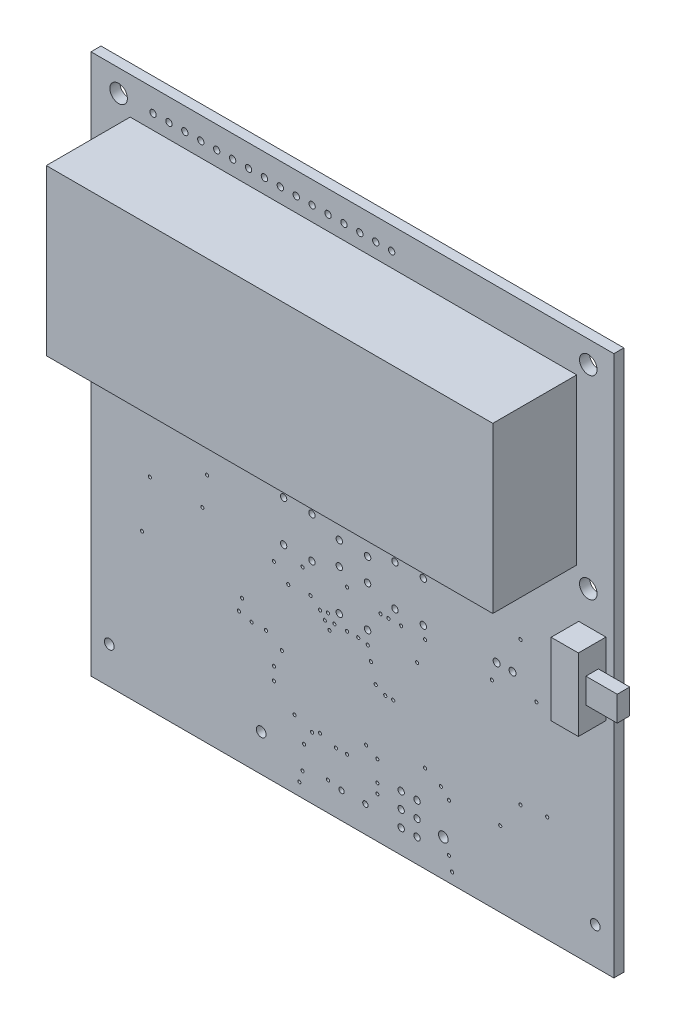
SolidWorks part; units mm, degrees
ref_plane "Front Plane" through (0, 0, 0) normal (0, 0, 1) x (1, 0, 0)
ref_plane "Top Plane" through (0, 0, 0) normal (0, 1, 0) x (1, 0, 0)
ref_plane "Right Plane" through (0, 0, 0) normal (1, 0, 0) x (0, 0, -1)
sketch "20" plane through (0, 0, 0) normal (0, 0, 1) x (1, 0, 0)
  line L0 (0, 86.36) -> (0, 0.02)
  line L1 (0, 0.02) -> (83.49, 0.02)
  line L2 (83.49, 0.02) -> (83.49, 86.36)
  line L3 (83.49, 86.36) -> (0, 86.36)
  circle A1 centre (40.01, 4.232) radius 0.425
  circle A2 centre (43.81, 4.232) radius 0.425
  circle A3 centre (27.18, 5.91) radius 0.775
  circle A4 centre (2.92, 5.91) radius 0.775
  circle A5 centre (80.52, 5.91) radius 0.775
  circle A6 centre (56.26, 5.91) radius 0.775
  circle A7 centre (4.41, 82.81) radius 1.4
  circle A8 centre (4.41, 51.81) radius 1.4
  circle A9 centre (79.41, 82.81) radius 1.4
  circle A10 centre (79.41, 51.81) radius 1.4
sketch "21" plane through (0, 0, 0) normal (0, 0, 1) x (1, 0, 0)
  line L120 (37.9171, 5.014) -> (37.9171, 4.032)
  line L121 (37.9171, 4.032) -> (37.91, 4.032)
  line L122 (37.91, 5.032) -> (38.91, 5.032)
  line L123 (45.91, 4.032) -> (45.91, 5.032)
  line L124 (45.91, 5.032) -> (44.91, 5.032)
  line L125 (37.91, 1.032) -> (37.91, 0.032)
  line L126 (45.91, 1.032) -> (45.91, 0.032)
  line L127 (47.625, 59.69) -> (48.895, 59.69)
  line L128 (48.895, 59.69) -> (49.53, 59.055)
  line L129 (49.53, 57.785) -> (48.895, 57.15)
  line L130 (44.45, 59.055) -> (45.085, 59.69)
  line L131 (45.085, 59.69) -> (46.355, 59.69)
  line L132 (46.355, 59.69) -> (46.99, 59.055)
  line L133 (46.99, 57.785) -> (46.355, 57.15)
  line L134 (46.355, 57.15) -> (45.085, 57.15)
  line L135 (45.085, 57.15) -> (44.45, 57.785)
  line L136 (47.625, 59.69) -> (46.99, 59.055)
  line L137 (46.99, 57.785) -> (47.625, 57.15)
  line L138 (48.895, 57.15) -> (47.625, 57.15)
  line L139 (40.005, 59.69) -> (41.275, 59.69)
  line L140 (41.275, 59.69) -> (41.91, 59.055)
  line L141 (41.91, 57.785) -> (41.275, 57.15)
  line L142 (41.91, 59.055) -> (42.545, 59.69)
  line L143 (42.545, 59.69) -> (43.815, 59.69)
  line L144 (43.815, 59.69) -> (44.45, 59.055)
  line L145 (44.45, 57.785) -> (43.815, 57.15)
  line L146 (43.815, 57.15) -> (42.545, 57.15)
  line L147 (42.545, 57.15) -> (41.91, 57.785)
  line L148 (36.83, 59.055) -> (37.465, 59.69)
  line L149 (37.465, 59.69) -> (38.735, 59.69)
  line L150 (38.735, 59.69) -> (39.37, 59.055)
  line L151 (39.37, 57.785) -> (38.735, 57.15)
  line L152 (38.735, 57.15) -> (37.465, 57.15)
  line L153 (37.465, 57.15) -> (36.83, 57.785)
  line L154 (40.005, 59.69) -> (39.37, 59.055)
  line L155 (39.37, 57.785) -> (40.005, 57.15)
  line L156 (41.275, 57.15) -> (40.005, 57.15)
  line L157 (32.385, 59.69) -> (33.655, 59.69)
  line L158 (33.655, 59.69) -> (34.29, 59.055)
  line L159 (34.29, 57.785) -> (33.655, 57.15)
  line L160 (34.29, 59.055) -> (34.925, 59.69)
  line L161 (34.925, 59.69) -> (36.195, 59.69)
  line L162 (36.195, 59.69) -> (36.83, 59.055)
  line L163 (36.83, 57.785) -> (36.195, 57.15)
  line L164 (36.195, 57.15) -> (34.925, 57.15)
  line L165 (34.925, 57.15) -> (34.29, 57.785)
  line L166 (31.75, 59.055) -> (31.75, 57.785)
  line L167 (32.385, 59.69) -> (31.75, 59.055)
  line L168 (31.75, 57.785) -> (32.385, 57.15)
  line L169 (33.655, 57.15) -> (32.385, 57.15)
  line L170 (50.165, 59.69) -> (51.435, 59.69)
  line L171 (51.435, 59.69) -> (52.07, 59.055)
  line L172 (52.07, 59.055) -> (52.07, 57.785)
  line L173 (52.07, 57.785) -> (51.435, 57.15)
  line L174 (50.165, 59.69) -> (49.53, 59.055)
  line L175 (49.53, 57.785) -> (50.165, 57.15)
  line L176 (51.435, 57.15) -> (50.165, 57.15)
  line L181 (44.958, 29.591) -> (44.958, 33.909)
  line L182 (38.862, 33.909) -> (38.862, 29.591)
  line L183 (42.908, 28.702) -> (40.894, 28.702)
  line L184 (42.938, 34.798) -> (40.894, 34.798)
  line L189 (44.958, 39.751) -> (44.958, 44.069)
  line L190 (38.862, 44.069) -> (38.862, 39.751)
  line L191 (42.908, 38.862) -> (40.894, 38.862)
  line L192 (42.938, 44.958) -> (40.894, 44.958)
  line L193 (53.848, 34.671) -> (53.848, 38.989)
  line L194 (47.752, 38.989) -> (47.752, 34.671)
  line L195 (51.798, 33.782) -> (49.784, 33.782)
  line L196 (51.828, 39.878) -> (49.784, 39.878)
  line L197 (36.068, 34.671) -> (36.068, 38.989)
  line L198 (29.972, 38.989) -> (29.972, 34.671)
  line L199 (34.018, 33.782) -> (32.004, 33.782)
  line L200 (34.048, 39.878) -> (32.004, 39.878)
  line L201 (82.185, 46.455) -> (77.835, 46.455)
  line L202 (77.835, 46.455) -> (77.835, 34.825)
  line L203 (77.835, 34.825) -> (82.185, 34.825)
  line L204 (82.185, 34.825) -> (82.185, 46.455)
  line L268 (25.259, 29.305) -> (29.658, 29.305)
  line L269 (29.658, 29.305) -> (29.658, 23.971)
  line L270 (29.558, 7.361) -> (29.558, 0.322)
  line L271 (29.558, 0.322) -> (28.14, 0.31)
  line L272 (0.913, 6.199) -> (0.913, 0.322)
  line L273 (0.913, 0.322) -> (1.891, 0.322)
  line L274 (1.002, 29.305) -> (0.913, 29.305)
  line L275 (0.913, 29.305) -> (0.913, 23.971)
  line L276 (78.599, 29.305) -> (82.998, 29.305)
  line L277 (82.998, 29.305) -> (82.998, 23.971)
  line L278 (82.898, 7.361) -> (82.898, 0.322)
  line L279 (82.898, 0.322) -> (81.48, 0.31)
  line L280 (54.253, 6.199) -> (54.253, 0.322)
  line L281 (54.253, 0.322) -> (55.231, 0.322)
  line L282 (54.342, 29.305) -> (54.253, 29.305)
  line L283 (54.253, 29.305) -> (54.253, 23.971)
  line L284 (1.91, 85.31) -> (81.91, 85.31)
  line L285 (81.91, 85.31) -> (81.91, 49.31)
  line L286 (81.91, 49.31) -> (1.91, 49.31)
  line L287 (1.91, 49.31) -> (1.91, 85.31)
  line L288 (6.26, 80.46) -> (77.56, 80.46)
  line L289 (77.56, 80.46) -> (77.56, 54.16)
  line L290 (77.56, 54.16) -> (6.26, 54.16)
  line L291 (6.26, 54.16) -> (6.26, 80.46)
  arc A255 (37.8409, 4.032) -> (37.9933, 4.032) centre (37.9171, 4.032) ccw
  arc A256 (37.9933, 5.014) -> (37.8409, 5.014) centre (37.9171, 5.014) ccw
  arc A257 (37.91, 4.1082) -> (37.91, 3.9558) centre (37.91, 4.032) ccw
  arc A258 (37.9171, 3.9558) -> (37.9171, 4.1082) centre (37.9171, 4.032) ccw
  arc A259 (38.91, 4.9558) -> (38.91, 5.1082) centre (38.91, 5.032) ccw
  arc A260 (37.91, 5.1082) -> (37.91, 4.9558) centre (37.91, 5.032) ccw
  arc A261 (45.9862, 5.032) -> (45.8338, 5.032) centre (45.91, 5.032) ccw
  arc A262 (45.8338, 4.032) -> (45.9862, 4.032) centre (45.91, 4.032) ccw
  arc A263 (44.91, 5.1082) -> (44.91, 4.9558) centre (44.91, 5.032) ccw
  arc A264 (45.91, 4.9558) -> (45.91, 5.1082) centre (45.91, 5.032) ccw
  arc A265 (37.8338, 0.032) -> (37.9862, 0.032) centre (37.91, 0.032) ccw
  arc A266 (37.9862, 1.032) -> (37.8338, 1.032) centre (37.91, 1.032) ccw
  arc A267 (45.8338, 0.032) -> (45.9862, 0.032) centre (45.91, 0.032) ccw
  arc A268 (45.9862, 1.032) -> (45.8338, 1.032) centre (45.91, 1.032) ccw
  arc A269 (48.895, 59.6392) -> (48.895, 59.7408) centre (48.895, 59.69) ccw
  arc A270 (47.625, 59.7408) -> (47.625, 59.6392) centre (47.625, 59.69) ccw
  arc A271 (49.4941, 59.0191) -> (49.5659, 59.0909) centre (49.53, 59.055) ccw
  arc A272 (48.9309, 59.7259) -> (48.8591, 59.6541) centre (48.895, 59.69) ccw
  arc A273 (48.8591, 57.1859) -> (48.9309, 57.1141) centre (48.895, 57.15) ccw
  arc A274 (49.5659, 57.7491) -> (49.4941, 57.8209) centre (49.53, 57.785) ccw
  arc A275 (45.1209, 59.6541) -> (45.0491, 59.7259) centre (45.085, 59.69) ccw
  arc A276 (44.4141, 59.0909) -> (44.4859, 59.0191) centre (44.45, 59.055) ccw
  arc A277 (46.355, 59.6392) -> (46.355, 59.7408) centre (46.355, 59.69) ccw
  arc A278 (45.085, 59.7408) -> (45.085, 59.6392) centre (45.085, 59.69) ccw
  arc A279 (46.9541, 59.0191) -> (47.0259, 59.0909) centre (46.99, 59.055) ccw
  arc A280 (46.3909, 59.7259) -> (46.3191, 59.6541) centre (46.355, 59.69) ccw
  arc A281 (46.3191, 57.1859) -> (46.3909, 57.1141) centre (46.355, 57.15) ccw
  arc A282 (47.0259, 57.7491) -> (46.9541, 57.8209) centre (46.99, 57.785) ccw
  arc A283 (45.085, 57.2008) -> (45.085, 57.0992) centre (45.085, 57.15) ccw
  arc A284 (46.355, 57.0992) -> (46.355, 57.2008) centre (46.355, 57.15) ccw
  arc A285 (44.4859, 57.8209) -> (44.4141, 57.7491) centre (44.45, 57.785) ccw
  arc A286 (45.0491, 57.1141) -> (45.1209, 57.1859) centre (45.085, 57.15) ccw
  arc A287 (46.9541, 59.0909) -> (47.0259, 59.0191) centre (46.99, 59.055) ccw
  arc A288 (47.6609, 59.6541) -> (47.5891, 59.7259) centre (47.625, 59.69) ccw
  arc A289 (47.5891, 57.1141) -> (47.6609, 57.1859) centre (47.625, 57.15) ccw
  arc A290 (47.0259, 57.8209) -> (46.9541, 57.7491) centre (46.99, 57.785) ccw
  arc A291 (47.625, 57.2008) -> (47.625, 57.0992) centre (47.625, 57.15) ccw
  arc A292 (48.895, 57.0992) -> (48.895, 57.2008) centre (48.895, 57.15) ccw
  arc A293 (41.275, 59.6392) -> (41.275, 59.7408) centre (41.275, 59.69) ccw
  arc A294 (40.005, 59.7408) -> (40.005, 59.6392) centre (40.005, 59.69) ccw
  arc A295 (41.8741, 59.0191) -> (41.9459, 59.0909) centre (41.91, 59.055) ccw
  arc A296 (41.3109, 59.7259) -> (41.2391, 59.6541) centre (41.275, 59.69) ccw
  arc A297 (41.2391, 57.1859) -> (41.3109, 57.1141) centre (41.275, 57.15) ccw
  arc A298 (41.9459, 57.7491) -> (41.8741, 57.8209) centre (41.91, 57.785) ccw
  arc A299 (42.5809, 59.6541) -> (42.5091, 59.7259) centre (42.545, 59.69) ccw
  arc A300 (41.8741, 59.0909) -> (41.9459, 59.0191) centre (41.91, 59.055) ccw
  arc A301 (43.815, 59.6392) -> (43.815, 59.7408) centre (43.815, 59.69) ccw
  arc A302 (42.545, 59.7408) -> (42.545, 59.6392) centre (42.545, 59.69) ccw
  arc A303 (44.4141, 59.0191) -> (44.4859, 59.0909) centre (44.45, 59.055) ccw
  arc A304 (43.8509, 59.7259) -> (43.7791, 59.6541) centre (43.815, 59.69) ccw
  arc A305 (43.7791, 57.1859) -> (43.8509, 57.1141) centre (43.815, 57.15) ccw
  arc A306 (44.4859, 57.7491) -> (44.4141, 57.8209) centre (44.45, 57.785) ccw
  arc A307 (42.545, 57.2008) -> (42.545, 57.0992) centre (42.545, 57.15) ccw
  arc A308 (43.815, 57.0992) -> (43.815, 57.2008) centre (43.815, 57.15) ccw
  arc A309 (41.9459, 57.8209) -> (41.8741, 57.7491) centre (41.91, 57.785) ccw
  arc A310 (42.5091, 57.1141) -> (42.5809, 57.1859) centre (42.545, 57.15) ccw
  arc A311 (37.5009, 59.6541) -> (37.4291, 59.7259) centre (37.465, 59.69) ccw
  arc A312 (36.7941, 59.0909) -> (36.8659, 59.0191) centre (36.83, 59.055) ccw
  arc A313 (38.735, 59.6392) -> (38.735, 59.7408) centre (38.735, 59.69) ccw
  arc A314 (37.465, 59.7408) -> (37.465, 59.6392) centre (37.465, 59.69) ccw
  arc A315 (39.3341, 59.0191) -> (39.4059, 59.0909) centre (39.37, 59.055) ccw
  arc A316 (38.7709, 59.7259) -> (38.6991, 59.6541) centre (38.735, 59.69) ccw
  arc A317 (38.6991, 57.1859) -> (38.7709, 57.1141) centre (38.735, 57.15) ccw
  arc A318 (39.4059, 57.7491) -> (39.3341, 57.8209) centre (39.37, 57.785) ccw
  arc A319 (37.465, 57.2008) -> (37.465, 57.0992) centre (37.465, 57.15) ccw
  arc A320 (38.735, 57.0992) -> (38.735, 57.2008) centre (38.735, 57.15) ccw
  arc A321 (36.8659, 57.8209) -> (36.7941, 57.7491) centre (36.83, 57.785) ccw
  arc A322 (37.4291, 57.1141) -> (37.5009, 57.1859) centre (37.465, 57.15) ccw
  arc A323 (39.3341, 59.0909) -> (39.4059, 59.0191) centre (39.37, 59.055) ccw
  arc A324 (40.0409, 59.6541) -> (39.9691, 59.7259) centre (40.005, 59.69) ccw
  arc A325 (39.9691, 57.1141) -> (40.0409, 57.1859) centre (40.005, 57.15) ccw
  arc A326 (39.4059, 57.8209) -> (39.3341, 57.7491) centre (39.37, 57.785) ccw
  arc A327 (40.005, 57.2008) -> (40.005, 57.0992) centre (40.005, 57.15) ccw
  arc A328 (41.275, 57.0992) -> (41.275, 57.2008) centre (41.275, 57.15) ccw
  arc A329 (33.655, 59.6392) -> (33.655, 59.7408) centre (33.655, 59.69) ccw
  arc A330 (32.385, 59.7408) -> (32.385, 59.6392) centre (32.385, 59.69) ccw
  arc A331 (34.2541, 59.0191) -> (34.3259, 59.0909) centre (34.29, 59.055) ccw
  arc A332 (33.6909, 59.7259) -> (33.6191, 59.6541) centre (33.655, 59.69) ccw
  arc A333 (33.6191, 57.1859) -> (33.6909, 57.1141) centre (33.655, 57.15) ccw
  arc A334 (34.3259, 57.7491) -> (34.2541, 57.8209) centre (34.29, 57.785) ccw
  arc A335 (34.9609, 59.6541) -> (34.8891, 59.7259) centre (34.925, 59.69) ccw
  arc A336 (34.2541, 59.0909) -> (34.3259, 59.0191) centre (34.29, 59.055) ccw
  arc A337 (36.195, 59.6392) -> (36.195, 59.7408) centre (36.195, 59.69) ccw
  arc A338 (34.925, 59.7408) -> (34.925, 59.6392) centre (34.925, 59.69) ccw
  arc A339 (36.7941, 59.0191) -> (36.8659, 59.0909) centre (36.83, 59.055) ccw
  arc A340 (36.2309, 59.7259) -> (36.1591, 59.6541) centre (36.195, 59.69) ccw
  arc A341 (36.1591, 57.1859) -> (36.2309, 57.1141) centre (36.195, 57.15) ccw
  arc A342 (36.8659, 57.7491) -> (36.7941, 57.8209) centre (36.83, 57.785) ccw
  arc A343 (34.925, 57.2008) -> (34.925, 57.0992) centre (34.925, 57.15) ccw
  arc A344 (36.195, 57.0992) -> (36.195, 57.2008) centre (36.195, 57.15) ccw
  arc A345 (34.3259, 57.8209) -> (34.2541, 57.7491) centre (34.29, 57.785) ccw
  arc A346 (34.8891, 57.1141) -> (34.9609, 57.1859) centre (34.925, 57.15) ccw
  arc A347 (31.6992, 57.785) -> (31.8008, 57.785) centre (31.75, 57.785) ccw
  arc A348 (31.8008, 59.055) -> (31.6992, 59.055) centre (31.75, 59.055) ccw
  arc A349 (31.7141, 59.0909) -> (31.7859, 59.0191) centre (31.75, 59.055) ccw
  arc A350 (32.4209, 59.6541) -> (32.3491, 59.7259) centre (32.385, 59.69) ccw
  arc A351 (32.3491, 57.1141) -> (32.4209, 57.1859) centre (32.385, 57.15) ccw
  arc A352 (31.7859, 57.8209) -> (31.7141, 57.7491) centre (31.75, 57.785) ccw
  arc A353 (32.385, 57.2008) -> (32.385, 57.0992) centre (32.385, 57.15) ccw
  arc A354 (33.655, 57.0992) -> (33.655, 57.2008) centre (33.655, 57.15) ccw
  arc A355 (51.435, 59.6392) -> (51.435, 59.7408) centre (51.435, 59.69) ccw
  arc A356 (50.165, 59.7408) -> (50.165, 59.6392) centre (50.165, 59.69) ccw
  arc A357 (52.0341, 59.0191) -> (52.1059, 59.0909) centre (52.07, 59.055) ccw
  arc A358 (51.4709, 59.7259) -> (51.3991, 59.6541) centre (51.435, 59.69) ccw
  arc A359 (52.0192, 57.785) -> (52.1208, 57.785) centre (52.07, 57.785) ccw
  arc A360 (52.1208, 59.055) -> (52.0192, 59.055) centre (52.07, 59.055) ccw
  arc A361 (51.3991, 57.1859) -> (51.4709, 57.1141) centre (51.435, 57.15) ccw
  arc A362 (52.1059, 57.7491) -> (52.0341, 57.8209) centre (52.07, 57.785) ccw
  arc A363 (49.4941, 59.0909) -> (49.5659, 59.0191) centre (49.53, 59.055) ccw
  arc A364 (50.2009, 59.6541) -> (50.1291, 59.7259) centre (50.165, 59.69) ccw
  arc A365 (50.1291, 57.1141) -> (50.2009, 57.1859) centre (50.165, 57.15) ccw
  arc A366 (49.5659, 57.8209) -> (49.4941, 57.7491) centre (49.53, 57.785) ccw
  arc A367 (50.165, 57.2008) -> (50.165, 57.0992) centre (50.165, 57.15) ccw
  arc A368 (51.435, 57.0992) -> (51.435, 57.2008) centre (51.435, 57.15) ccw
  arc A377 (45.0088, 33.909) -> (44.9072, 33.909) centre (44.958, 33.909) ccw
  arc A378 (44.9072, 29.591) -> (45.0088, 29.591) centre (44.958, 29.591) ccw
  arc A379 (38.8112, 29.591) -> (38.9128, 29.591) centre (38.862, 29.591) ccw
  arc A380 (38.9128, 33.909) -> (38.8112, 33.909) centre (38.862, 33.909) ccw
  arc A381 (40.894, 28.7528) -> (40.894, 28.6512) centre (40.894, 28.702) ccw
  arc A382 (42.908, 28.6512) -> (42.908, 28.7528) centre (42.908, 28.702) ccw
  arc A383 (40.894, 34.8488) -> (40.894, 34.7472) centre (40.894, 34.798) ccw
  arc A384 (42.938, 34.7472) -> (42.938, 34.8488) centre (42.938, 34.798) ccw
  circle A385 centre (41.91, 31.75) radius 1.778
  arc A395 (45.0088, 44.069) -> (44.9072, 44.069) centre (44.958, 44.069) ccw
  arc A396 (44.9072, 39.751) -> (45.0088, 39.751) centre (44.958, 39.751) ccw
  arc A397 (38.8112, 39.751) -> (38.9128, 39.751) centre (38.862, 39.751) ccw
  arc A398 (38.9128, 44.069) -> (38.8112, 44.069) centre (38.862, 44.069) ccw
  arc A399 (40.894, 38.9128) -> (40.894, 38.8112) centre (40.894, 38.862) ccw
  arc A400 (42.908, 38.8112) -> (42.908, 38.9128) centre (42.908, 38.862) ccw
  arc A401 (40.894, 45.0088) -> (40.894, 44.9072) centre (40.894, 44.958) ccw
  arc A402 (42.938, 44.9072) -> (42.938, 45.0088) centre (42.938, 44.958) ccw
  circle A403 centre (41.91, 41.91) radius 1.778
  arc A404 (53.8988, 38.989) -> (53.7972, 38.989) centre (53.848, 38.989) ccw
  arc A405 (53.7972, 34.671) -> (53.8988, 34.671) centre (53.848, 34.671) ccw
  arc A406 (47.7012, 34.671) -> (47.8028, 34.671) centre (47.752, 34.671) ccw
  arc A407 (47.8028, 38.989) -> (47.7012, 38.989) centre (47.752, 38.989) ccw
  arc A408 (49.784, 33.8328) -> (49.784, 33.7312) centre (49.784, 33.782) ccw
  arc A409 (51.798, 33.7312) -> (51.798, 33.8328) centre (51.798, 33.782) ccw
  arc A410 (49.784, 39.9288) -> (49.784, 39.8272) centre (49.784, 39.878) ccw
  arc A411 (51.828, 39.8272) -> (51.828, 39.9288) centre (51.828, 39.878) ccw
  circle A412 centre (50.8, 36.83) radius 1.778
  arc A413 (36.1188, 38.989) -> (36.0172, 38.989) centre (36.068, 38.989) ccw
  arc A414 (36.0172, 34.671) -> (36.1188, 34.671) centre (36.068, 34.671) ccw
  arc A415 (29.9212, 34.671) -> (30.0228, 34.671) centre (29.972, 34.671) ccw
  arc A416 (30.0228, 38.989) -> (29.9212, 38.989) centre (29.972, 38.989) ccw
  arc A417 (32.004, 33.8328) -> (32.004, 33.7312) centre (32.004, 33.782) ccw
  arc A418 (34.018, 33.7312) -> (34.018, 33.8328) centre (34.018, 33.782) ccw
  arc A419 (32.004, 39.9288) -> (32.004, 39.8272) centre (32.004, 39.878) ccw
  arc A420 (34.048, 39.8272) -> (34.048, 39.9288) centre (34.048, 39.878) ccw
  circle A421 centre (33.02, 36.83) radius 1.778
  arc A422 (77.835, 46.5058) -> (77.835, 46.4042) centre (77.835, 46.455) ccw
  arc A423 (82.185, 46.4042) -> (82.185, 46.5058) centre (82.185, 46.455) ccw
  arc A424 (77.7842, 34.825) -> (77.8858, 34.825) centre (77.835, 34.825) ccw
  arc A425 (77.8858, 46.455) -> (77.7842, 46.455) centre (77.835, 46.455) ccw
  arc A426 (82.185, 34.7742) -> (82.185, 34.8758) centre (82.185, 34.825) ccw
  arc A427 (77.835, 34.8758) -> (77.835, 34.7742) centre (77.835, 34.825) ccw
  arc A428 (82.2358, 46.455) -> (82.1342, 46.455) centre (82.185, 46.455) ccw
  arc A429 (82.1342, 34.825) -> (82.2358, 34.825) centre (82.185, 34.825) ccw
  arc A569 (29.658, 29.2415) -> (29.658, 29.3685) centre (29.658, 29.305) ccw
  arc A570 (25.259, 29.3685) -> (25.259, 29.2415) centre (25.259, 29.305) ccw
  arc A571 (29.5945, 23.971) -> (29.7215, 23.971) centre (29.658, 23.971) ccw
  arc A572 (29.7215, 29.305) -> (29.5945, 29.305) centre (29.658, 29.305) ccw
  arc A573 (29.4945, 0.322) -> (29.6215, 0.322) centre (29.558, 0.322) ccw
  arc A574 (29.6215, 7.361) -> (29.4945, 7.361) centre (29.558, 7.361) ccw
  arc A575 (28.1395, 0.3735) -> (28.1405, 0.2465) centre (28.14, 0.31) ccw
  arc A576 (29.5585, 0.2585) -> (29.5575, 0.3855) centre (29.558, 0.322) ccw
  arc A577 (0.8495, 0.322) -> (0.9765, 0.322) centre (0.913, 0.322) ccw
  arc A578 (0.9765, 6.199) -> (0.8495, 6.199) centre (0.913, 6.199) ccw
  arc A579 (1.891, 0.2585) -> (1.891, 0.3855) centre (1.891, 0.322) ccw
  arc A580 (0.913, 0.3855) -> (0.913, 0.2585) centre (0.913, 0.322) ccw
  arc A581 (0.913, 29.3685) -> (0.913, 29.2415) centre (0.913, 29.305) ccw
  arc A582 (1.002, 29.2415) -> (1.002, 29.3685) centre (1.002, 29.305) ccw
  arc A583 (0.8495, 23.971) -> (0.9765, 23.971) centre (0.913, 23.971) ccw
  arc A584 (0.9765, 29.305) -> (0.8495, 29.305) centre (0.913, 29.305) ccw
  arc A585 (82.998, 29.2415) -> (82.998, 29.3685) centre (82.998, 29.305) ccw
  arc A586 (78.599, 29.3685) -> (78.599, 29.2415) centre (78.599, 29.305) ccw
  arc A587 (82.9345, 23.971) -> (83.0615, 23.971) centre (82.998, 23.971) ccw
  arc A588 (83.0615, 29.305) -> (82.9345, 29.305) centre (82.998, 29.305) ccw
  arc A589 (82.8345, 0.322) -> (82.9615, 0.322) centre (82.898, 0.322) ccw
  arc A590 (82.9615, 7.361) -> (82.8345, 7.361) centre (82.898, 7.361) ccw
  arc A591 (81.4795, 0.3735) -> (81.4805, 0.2465) centre (81.48, 0.31) ccw
  arc A592 (82.8985, 0.2585) -> (82.8975, 0.3855) centre (82.898, 0.322) ccw
  arc A593 (54.1895, 0.322) -> (54.3165, 0.322) centre (54.253, 0.322) ccw
  arc A594 (54.3165, 6.199) -> (54.1895, 6.199) centre (54.253, 6.199) ccw
  arc A595 (55.231, 0.2585) -> (55.231, 0.3855) centre (55.231, 0.322) ccw
  arc A596 (54.253, 0.3855) -> (54.253, 0.2585) centre (54.253, 0.322) ccw
  arc A597 (54.253, 29.3685) -> (54.253, 29.2415) centre (54.253, 29.305) ccw
  arc A598 (54.342, 29.2415) -> (54.342, 29.3685) centre (54.342, 29.305) ccw
  arc A599 (54.1895, 23.971) -> (54.3165, 23.971) centre (54.253, 23.971) ccw
  arc A600 (54.3165, 29.305) -> (54.1895, 29.305) centre (54.253, 29.305) ccw
  arc A601 (81.91, 85.2592) -> (81.91, 85.3608) centre (81.91, 85.31) ccw
  arc A602 (1.91, 85.3608) -> (1.91, 85.2592) centre (1.91, 85.31) ccw
  arc A603 (81.8592, 49.31) -> (81.9608, 49.31) centre (81.91, 49.31) ccw
  arc A604 (81.9608, 85.31) -> (81.8592, 85.31) centre (81.91, 85.31) ccw
  arc A605 (1.91, 49.3608) -> (1.91, 49.2592) centre (1.91, 49.31) ccw
  arc A606 (81.91, 49.2592) -> (81.91, 49.3608) centre (81.91, 49.31) ccw
  arc A607 (1.9608, 85.31) -> (1.8592, 85.31) centre (1.91, 85.31) ccw
  arc A608 (1.8592, 49.31) -> (1.9608, 49.31) centre (1.91, 49.31) ccw
  arc A609 (77.56, 80.4092) -> (77.56, 80.5108) centre (77.56, 80.46) ccw
  arc A610 (6.26, 80.5108) -> (6.26, 80.4092) centre (6.26, 80.46) ccw
  arc A611 (77.5092, 54.16) -> (77.6108, 54.16) centre (77.56, 54.16) ccw
  arc A612 (77.6108, 80.46) -> (77.5092, 80.46) centre (77.56, 80.46) ccw
  arc A613 (6.26, 54.2108) -> (6.26, 54.1092) centre (6.26, 54.16) ccw
  arc A614 (77.56, 54.1092) -> (77.56, 54.2108) centre (77.56, 54.16) ccw
  arc A615 (6.3108, 80.46) -> (6.2092, 80.46) centre (6.26, 80.46) ccw
  arc A616 (6.2092, 54.16) -> (6.3108, 54.16) centre (6.26, 54.16) ccw
sketch "51" plane through (0, 0, 0) normal (0, 0, 1) x (1, 0, 0)
  line L199 (42.926, 28.702) -> (44.45, 28.702)
  line L200 (44.45, 28.702) -> (44.958, 29.21)
  line L201 (38.862, 29.21) -> (39.37, 28.702)
  line L202 (39.37, 28.702) -> (40.894, 28.702)
  line L203 (44.958, 34.29) -> (44.45, 34.798)
  line L204 (44.45, 34.798) -> (42.926, 34.798)
  line L205 (38.862, 34.29) -> (39.37, 34.798)
  line L206 (39.37, 34.798) -> (40.894, 34.798)
  line L207 (38.862, 29.21) -> (38.862, 29.591)
  line L208 (38.862, 34.29) -> (38.862, 33.909)
  line L209 (44.958, 34.29) -> (44.958, 33.909)
  line L210 (44.958, 29.21) -> (44.958, 29.591)
  line L211 (43.18, 34.29) -> (42.418, 34.29)
  line L212 (41.402, 34.29) -> (40.64, 34.29)
  line L213 (42.418, 34.29) -> (41.529, 33.909)
  line L221 (42.926, 38.862) -> (44.45, 38.862)
  line L222 (44.45, 38.862) -> (44.958, 39.37)
  line L223 (38.862, 39.37) -> (39.37, 38.862)
  line L224 (39.37, 38.862) -> (40.894, 38.862)
  line L225 (44.958, 44.45) -> (44.45, 44.958)
  line L226 (44.45, 44.958) -> (42.926, 44.958)
  line L227 (38.862, 44.45) -> (39.37, 44.958)
  line L228 (39.37, 44.958) -> (40.894, 44.958)
  line L229 (38.862, 39.37) -> (38.862, 39.751)
  line L230 (38.862, 44.45) -> (38.862, 44.069)
  line L231 (44.958, 44.45) -> (44.958, 44.069)
  line L232 (44.958, 39.37) -> (44.958, 39.751)
  line L233 (43.18, 44.45) -> (42.418, 44.45)
  line L234 (41.402, 44.45) -> (40.64, 44.45)
  line L235 (42.418, 44.45) -> (41.529, 44.069)
  line L236 (51.816, 33.782) -> (53.34, 33.782)
  line L237 (53.34, 33.782) -> (53.848, 34.29)
  line L238 (47.752, 34.29) -> (48.26, 33.782)
  line L239 (48.26, 33.782) -> (49.784, 33.782)
  line L240 (53.848, 39.37) -> (53.34, 39.878)
  line L241 (53.34, 39.878) -> (51.816, 39.878)
  line L242 (47.752, 39.37) -> (48.26, 39.878)
  line L243 (48.26, 39.878) -> (49.784, 39.878)
  line L244 (47.752, 34.29) -> (47.752, 34.671)
  line L245 (47.752, 39.37) -> (47.752, 38.989)
  line L246 (53.848, 39.37) -> (53.848, 38.989)
  line L247 (53.848, 34.29) -> (53.848, 34.671)
  line L248 (52.07, 39.37) -> (51.308, 39.37)
  line L249 (50.292, 39.37) -> (49.53, 39.37)
  line L250 (51.308, 39.37) -> (50.419, 38.989)
  line L251 (34.036, 33.782) -> (35.56, 33.782)
  line L252 (35.56, 33.782) -> (36.068, 34.29)
  line L253 (29.972, 34.29) -> (30.48, 33.782)
  line L254 (30.48, 33.782) -> (32.004, 33.782)
  line L255 (36.068, 39.37) -> (35.56, 39.878)
  line L256 (35.56, 39.878) -> (34.036, 39.878)
  line L257 (29.972, 39.37) -> (30.48, 39.878)
  line L258 (30.48, 39.878) -> (32.004, 39.878)
  line L259 (29.972, 34.29) -> (29.972, 34.671)
  line L260 (29.972, 39.37) -> (29.972, 38.989)
  line L261 (36.068, 39.37) -> (36.068, 38.989)
  line L262 (36.068, 34.29) -> (36.068, 34.671)
  line L263 (34.29, 39.37) -> (33.528, 39.37)
  line L264 (32.512, 39.37) -> (31.75, 39.37)
  line L265 (33.528, 39.37) -> (32.639, 38.989)
  line L270 (29.49, 29.21) -> (29.49, 0.41)
  line L271 (29.49, 0.41) -> (25.24, 0.41)
  line L272 (25.24, 0.41) -> (4.74, 0.41)
  line L273 (4.74, 0.41) -> (0.99, 0.41)
  line L274 (0.99, 0.41) -> (0.99, 29.21)
  line L275 (0.99, 29.21) -> (29.49, 29.21)
  line L276 (27.24, -6.39) -> (2.24, -6.39)
  line L277 (25.24, 0.41) -> (25.24, 1.21)
  line L278 (15.24, 11.21) -> (14.74, 11.21)
  line L279 (4.74, 1.21) -> (4.74, 0.41)
  line L280 (6.7704, -4.8596) -> (6.1857, -4.8596)
  line L281 (6.1857, -4.8596) -> (5.9908, -5.0545)
  line L282 (5.9908, -5.0545) -> (5.9908, -5.4443)
  line L283 (5.9908, -5.4443) -> (6.1857, -5.6392)
  line L284 (6.1857, -5.6392) -> (6.7704, -5.6392)
  line L285 (7.3551, -4.8596) -> (7.7449, -4.8596)
  line L286 (7.7449, -4.8596) -> (7.9398, -5.0545)
  line L287 (7.9398, -5.0545) -> (7.9398, -5.6392)
  line L288 (7.9398, -5.6392) -> (7.3551, -5.6392)
  line L289 (7.3551, -5.6392) -> (7.1602, -5.4443)
  line L290 (7.1602, -5.4443) -> (7.3551, -5.2494)
  line L291 (7.3551, -5.2494) -> (7.9398, -5.2494)
  line L292 (8.3296, -5.6392) -> (8.3296, -4.8596)
  line L293 (8.3296, -5.2494) -> (8.7194, -4.8596)
  line L294 (8.7194, -4.8596) -> (8.9143, -4.8596)
  line L295 (10.0837, -4.4698) -> (10.0837, -5.6392)
  line L296 (10.0837, -5.6392) -> (9.499, -5.6392)
  line L297 (9.499, -5.6392) -> (9.3041, -5.4443)
  line L298 (9.3041, -5.4443) -> (9.3041, -5.0545)
  line L299 (9.3041, -5.0545) -> (9.499, -4.8596)
  line L300 (9.499, -4.8596) -> (10.0837, -4.8596)
  line L301 (11.6429, -4.4698) -> (11.8378, -4.4698)
  line L302 (11.8378, -4.4698) -> (11.8378, -5.6392)
  line L303 (11.6429, -5.6392) -> (12.0327, -5.6392)
  line L304 (12.6174, -5.6392) -> (13.0072, -5.6392)
  line L305 (13.0072, -5.6392) -> (13.2021, -5.4443)
  line L306 (13.2021, -5.4443) -> (13.2021, -5.0545)
  line L307 (13.2021, -5.0545) -> (13.0072, -4.8596)
  line L308 (13.0072, -4.8596) -> (12.6174, -4.8596)
  line L309 (12.6174, -4.8596) -> (12.4225, -5.0545)
  line L310 (12.4225, -5.0545) -> (12.4225, -5.4443)
  line L311 (12.4225, -5.4443) -> (12.6174, -5.6392)
  line L312 (14.3715, -4.8596) -> (13.7868, -4.8596)
  line L313 (13.7868, -4.8596) -> (13.5919, -5.0545)
  line L314 (13.5919, -5.0545) -> (13.5919, -5.4443)
  line L315 (13.5919, -5.4443) -> (13.7868, -5.6392)
  line L316 (13.7868, -5.6392) -> (14.3715, -5.6392)
  line L317 (14.7613, -5.6392) -> (14.7613, -4.4698)
  line L318 (15.346, -5.6392) -> (14.7613, -5.2494)
  line L319 (14.7613, -5.2494) -> (15.346, -4.8596)
  line L320 (16.9052, -6.029) -> (16.9052, -4.8596)
  line L321 (16.9052, -4.8596) -> (17.4899, -4.8596)
  line L322 (17.4899, -4.8596) -> (17.6848, -5.0545)
  line L323 (17.6848, -5.0545) -> (17.6848, -5.4443)
  line L324 (17.6848, -5.4443) -> (17.4899, -5.6392)
  line L325 (17.4899, -5.6392) -> (16.9052, -5.6392)
  line L326 (18.2695, -5.6392) -> (18.6593, -5.6392)
  line L327 (18.6593, -5.6392) -> (18.8542, -5.4443)
  line L328 (18.8542, -5.4443) -> (18.8542, -5.0545)
  line L329 (18.8542, -5.0545) -> (18.6593, -4.8596)
  line L330 (18.6593, -4.8596) -> (18.2695, -4.8596)
  line L331 (18.2695, -4.8596) -> (18.0746, -5.0545)
  line L332 (18.0746, -5.0545) -> (18.0746, -5.4443)
  line L333 (18.0746, -5.4443) -> (18.2695, -5.6392)
  line L334 (19.244, -5.6392) -> (19.8287, -5.6392)
  line L335 (19.8287, -5.6392) -> (20.0236, -5.4443)
  line L336 (20.0236, -5.4443) -> (19.8287, -5.2494)
  line L337 (19.8287, -5.2494) -> (19.4389, -5.2494)
  line L338 (19.4389, -5.2494) -> (19.244, -5.0545)
  line L339 (19.244, -5.0545) -> (19.4389, -4.8596)
  line L340 (19.4389, -4.8596) -> (20.0236, -4.8596)
  line L341 (20.4134, -4.8596) -> (20.6083, -4.8596)
  line L342 (20.6083, -4.8596) -> (20.6083, -5.6392)
  line L343 (20.4134, -5.6392) -> (20.8032, -5.6392)
  line L344 (20.6083, -4.2749) -> (20.6083, -4.4698)
  line L345 (21.3879, -4.6647) -> (21.3879, -5.4443)
  line L346 (21.3879, -5.4443) -> (21.5828, -5.6392)
  line L347 (21.193, -4.8596) -> (21.5828, -4.8596)
  line L348 (21.9726, -4.8596) -> (22.1675, -4.8596)
  line L349 (22.1675, -4.8596) -> (22.1675, -5.6392)
  line L350 (21.9726, -5.6392) -> (22.3624, -5.6392)
  line L351 (22.1675, -4.2749) -> (22.1675, -4.4698)
  line L352 (22.947, -5.6392) -> (23.3368, -5.6392)
  line L353 (23.3368, -5.6392) -> (23.5317, -5.4443)
  line L354 (23.5317, -5.4443) -> (23.5317, -5.0545)
  line L355 (23.5317, -5.0545) -> (23.3368, -4.8596)
  line L356 (23.3368, -4.8596) -> (22.947, -4.8596)
  line L357 (22.947, -4.8596) -> (22.7522, -5.0545)
  line L358 (22.7522, -5.0545) -> (22.7522, -5.4443)
  line L359 (22.7522, -5.4443) -> (22.947, -5.6392)
  line L360 (23.9215, -5.6392) -> (23.9215, -4.8596)
  line L361 (23.9215, -4.8596) -> (24.5062, -4.8596)
  line L362 (24.5062, -4.8596) -> (24.7011, -5.0545)
  line L363 (24.7011, -5.0545) -> (24.7011, -5.6392)
  line L364 (82.83, 29.21) -> (82.83, 0.41)
  line L365 (82.83, 0.41) -> (78.58, 0.41)
  line L366 (78.58, 0.41) -> (58.08, 0.41)
  line L367 (58.08, 0.41) -> (54.33, 0.41)
  line L368 (54.33, 0.41) -> (54.33, 29.21)
  line L369 (54.33, 29.21) -> (82.83, 29.21)
  line L370 (80.58, -6.39) -> (55.58, -6.39)
  line L371 (78.58, 0.41) -> (78.58, 1.21)
  line L372 (68.58, 11.21) -> (68.08, 11.21)
  line L373 (58.08, 1.21) -> (58.08, 0.41)
  line L374 (60.1104, -4.8596) -> (59.5257, -4.8596)
  line L375 (59.5257, -4.8596) -> (59.3308, -5.0545)
  line L376 (59.3308, -5.0545) -> (59.3308, -5.4443)
  line L377 (59.3308, -5.4443) -> (59.5257, -5.6392)
  line L378 (59.5257, -5.6392) -> (60.1104, -5.6392)
  line L379 (60.6951, -4.8596) -> (61.0849, -4.8596)
  line L380 (61.0849, -4.8596) -> (61.2798, -5.0545)
  line L381 (61.2798, -5.0545) -> (61.2798, -5.6392)
  line L382 (61.2798, -5.6392) -> (60.6951, -5.6392)
  line L383 (60.6951, -5.6392) -> (60.5002, -5.4443)
  line L384 (60.5002, -5.4443) -> (60.6951, -5.2494)
  line L385 (60.6951, -5.2494) -> (61.2798, -5.2494)
  line L386 (61.6696, -5.6392) -> (61.6696, -4.8596)
  line L387 (61.6696, -5.2494) -> (62.0594, -4.8596)
  line L388 (62.0594, -4.8596) -> (62.2543, -4.8596)
  line L389 (63.4237, -4.4698) -> (63.4237, -5.6392)
  line L390 (63.4237, -5.6392) -> (62.839, -5.6392)
  line L391 (62.839, -5.6392) -> (62.6441, -5.4443)
  line L392 (62.6441, -5.4443) -> (62.6441, -5.0545)
  line L393 (62.6441, -5.0545) -> (62.839, -4.8596)
  line L394 (62.839, -4.8596) -> (63.4237, -4.8596)
  line L395 (64.9829, -4.4698) -> (65.1778, -4.4698)
  line L396 (65.1778, -4.4698) -> (65.1778, -5.6392)
  line L397 (64.9829, -5.6392) -> (65.3727, -5.6392)
  line L398 (65.9574, -5.6392) -> (66.3472, -5.6392)
  line L399 (66.3472, -5.6392) -> (66.5421, -5.4443)
  line L400 (66.5421, -5.4443) -> (66.5421, -5.0545)
  line L401 (66.5421, -5.0545) -> (66.3472, -4.8596)
  line L402 (66.3472, -4.8596) -> (65.9574, -4.8596)
  line L403 (65.9574, -4.8596) -> (65.7625, -5.0545)
  line L404 (65.7625, -5.0545) -> (65.7625, -5.4443)
  line L405 (65.7625, -5.4443) -> (65.9574, -5.6392)
  line L406 (67.7115, -4.8596) -> (67.1268, -4.8596)
  line L407 (67.1268, -4.8596) -> (66.9319, -5.0545)
  line L408 (66.9319, -5.0545) -> (66.9319, -5.4443)
  line L409 (66.9319, -5.4443) -> (67.1268, -5.6392)
  line L410 (67.1268, -5.6392) -> (67.7115, -5.6392)
  line L411 (68.1013, -5.6392) -> (68.1013, -4.4698)
  line L412 (68.686, -5.6392) -> (68.1013, -5.2494)
  line L413 (68.1013, -5.2494) -> (68.686, -4.8596)
  line L414 (70.2452, -6.029) -> (70.2452, -4.8596)
  line L415 (70.2452, -4.8596) -> (70.8299, -4.8596)
  line L416 (70.8299, -4.8596) -> (71.0248, -5.0545)
  line L417 (71.0248, -5.0545) -> (71.0248, -5.4443)
  line L418 (71.0248, -5.4443) -> (70.8299, -5.6392)
  line L419 (70.8299, -5.6392) -> (70.2452, -5.6392)
  line L420 (71.6095, -5.6392) -> (71.9993, -5.6392)
  line L421 (71.9993, -5.6392) -> (72.1942, -5.4443)
  line L422 (72.1942, -5.4443) -> (72.1942, -5.0545)
  line L423 (72.1942, -5.0545) -> (71.9993, -4.8596)
  line L424 (71.9993, -4.8596) -> (71.6095, -4.8596)
  line L425 (71.6095, -4.8596) -> (71.4146, -5.0545)
  line L426 (71.4146, -5.0545) -> (71.4146, -5.4443)
  line L427 (71.4146, -5.4443) -> (71.6095, -5.6392)
  line L428 (72.584, -5.6392) -> (73.1687, -5.6392)
  line L429 (73.1687, -5.6392) -> (73.3636, -5.4443)
  line L430 (73.3636, -5.4443) -> (73.1687, -5.2494)
  line L431 (73.1687, -5.2494) -> (72.7789, -5.2494)
  line L432 (72.7789, -5.2494) -> (72.584, -5.0545)
  line L433 (72.584, -5.0545) -> (72.7789, -4.8596)
  line L434 (72.7789, -4.8596) -> (73.3636, -4.8596)
  line L435 (73.7534, -4.8596) -> (73.9483, -4.8596)
  line L436 (73.9483, -4.8596) -> (73.9483, -5.6392)
  line L437 (73.7534, -5.6392) -> (74.1432, -5.6392)
  line L438 (73.9483, -4.2749) -> (73.9483, -4.4698)
  line L439 (74.7279, -4.6647) -> (74.7279, -5.4443)
  line L440 (74.7279, -5.4443) -> (74.9228, -5.6392)
  line L441 (74.533, -4.8596) -> (74.9228, -4.8596)
  line L442 (75.3126, -4.8596) -> (75.5075, -4.8596)
  line L443 (75.5075, -4.8596) -> (75.5075, -5.6392)
  line L444 (75.3126, -5.6392) -> (75.7024, -5.6392)
  line L445 (75.5075, -4.2749) -> (75.5075, -4.4698)
  line L446 (76.287, -5.6392) -> (76.6768, -5.6392)
  line L447 (76.6768, -5.6392) -> (76.8717, -5.4443)
  line L448 (76.8717, -5.4443) -> (76.8717, -5.0545)
  line L449 (76.8717, -5.0545) -> (76.6768, -4.8596)
  line L450 (76.6768, -4.8596) -> (76.287, -4.8596)
  line L451 (76.287, -4.8596) -> (76.0922, -5.0545)
  line L452 (76.0922, -5.0545) -> (76.0922, -5.4443)
  line L453 (76.0922, -5.4443) -> (76.287, -5.6392)
  line L454 (77.2615, -5.6392) -> (77.2615, -4.8596)
  line L455 (77.2615, -4.8596) -> (77.8462, -4.8596)
  line L456 (77.8462, -4.8596) -> (78.0411, -5.0545)
  line L457 (78.0411, -5.0545) -> (78.0411, -5.6392)
  arc A398 (44.45, 28.6512) -> (44.45, 28.7528) centre (44.45, 28.702) ccw
  arc A399 (42.926, 28.7528) -> (42.926, 28.6512) centre (42.926, 28.702) ccw
  arc A400 (44.9939, 29.1741) -> (44.9221, 29.2459) centre (44.958, 29.21) ccw
  arc A401 (44.4141, 28.7379) -> (44.4859, 28.6661) centre (44.45, 28.702) ccw
  arc A402 (39.3341, 28.6661) -> (39.4059, 28.7379) centre (39.37, 28.702) ccw
  arc A403 (38.8979, 29.2459) -> (38.8261, 29.1741) centre (38.862, 29.21) ccw
  arc A404 (40.894, 28.6512) -> (40.894, 28.7528) centre (40.894, 28.702) ccw
  arc A405 (39.37, 28.7528) -> (39.37, 28.6512) centre (39.37, 28.702) ccw
  arc A406 (44.4859, 34.8339) -> (44.4141, 34.7621) centre (44.45, 34.798) ccw
  arc A407 (44.9221, 34.2541) -> (44.9939, 34.3259) centre (44.958, 34.29) ccw
  arc A408 (42.926, 34.8488) -> (42.926, 34.7472) centre (42.926, 34.798) ccw
  arc A409 (44.45, 34.7472) -> (44.45, 34.8488) centre (44.45, 34.798) ccw
  arc A410 (39.4059, 34.7621) -> (39.3341, 34.8339) centre (39.37, 34.798) ccw
  arc A411 (38.8261, 34.3259) -> (38.8979, 34.2541) centre (38.862, 34.29) ccw
  arc A412 (40.894, 34.7472) -> (40.894, 34.8488) centre (40.894, 34.798) ccw
  arc A413 (39.37, 34.8488) -> (39.37, 34.7472) centre (39.37, 34.798) ccw
  arc A414 (38.9128, 29.591) -> (38.8112, 29.591) centre (38.862, 29.591) ccw
  arc A415 (38.8112, 29.21) -> (38.9128, 29.21) centre (38.862, 29.21) ccw
  arc A416 (38.8112, 33.909) -> (38.9128, 33.909) centre (38.862, 33.909) ccw
  arc A417 (38.9128, 34.29) -> (38.8112, 34.29) centre (38.862, 34.29) ccw
  arc A418 (44.9072, 33.909) -> (45.0088, 33.909) centre (44.958, 33.909) ccw
  arc A419 (45.0088, 34.29) -> (44.9072, 34.29) centre (44.958, 34.29) ccw
  arc A420 (45.0088, 29.591) -> (44.9072, 29.591) centre (44.958, 29.591) ccw
  arc A421 (44.9072, 29.21) -> (45.0088, 29.21) centre (44.958, 29.21) ccw
  arc A422 (42.418, 34.3408) -> (42.418, 34.2392) centre (42.418, 34.29) ccw
  arc A423 (43.18, 34.2392) -> (43.18, 34.3408) centre (43.18, 34.29) ccw
  arc A424 (40.64, 34.3408) -> (40.64, 34.2392) centre (40.64, 34.29) ccw
  arc A425 (41.402, 34.2392) -> (41.402, 34.3408) centre (41.402, 34.29) ccw
  arc A426 (41.509, 33.9557) -> (41.549, 33.8623) centre (41.529, 33.909) ccw
  arc A427 (42.438, 34.2433) -> (42.398, 34.3367) centre (42.418, 34.29) ccw
  arc A442 (44.45, 38.8112) -> (44.45, 38.9128) centre (44.45, 38.862) ccw
  arc A443 (42.926, 38.9128) -> (42.926, 38.8112) centre (42.926, 38.862) ccw
  arc A444 (44.9939, 39.3341) -> (44.9221, 39.4059) centre (44.958, 39.37) ccw
  arc A445 (44.4141, 38.8979) -> (44.4859, 38.8261) centre (44.45, 38.862) ccw
  arc A446 (39.3341, 38.8261) -> (39.4059, 38.8979) centre (39.37, 38.862) ccw
  arc A447 (38.8979, 39.4059) -> (38.8261, 39.3341) centre (38.862, 39.37) ccw
  arc A448 (40.894, 38.8112) -> (40.894, 38.9128) centre (40.894, 38.862) ccw
  arc A449 (39.37, 38.9128) -> (39.37, 38.8112) centre (39.37, 38.862) ccw
  arc A450 (44.4859, 44.9939) -> (44.4141, 44.9221) centre (44.45, 44.958) ccw
  arc A451 (44.9221, 44.4141) -> (44.9939, 44.4859) centre (44.958, 44.45) ccw
  arc A452 (42.926, 45.0088) -> (42.926, 44.9072) centre (42.926, 44.958) ccw
  arc A453 (44.45, 44.9072) -> (44.45, 45.0088) centre (44.45, 44.958) ccw
  arc A454 (39.4059, 44.9221) -> (39.3341, 44.9939) centre (39.37, 44.958) ccw
  arc A455 (38.8261, 44.4859) -> (38.8979, 44.4141) centre (38.862, 44.45) ccw
  arc A456 (40.894, 44.9072) -> (40.894, 45.0088) centre (40.894, 44.958) ccw
  arc A457 (39.37, 45.0088) -> (39.37, 44.9072) centre (39.37, 44.958) ccw
  arc A458 (38.9128, 39.751) -> (38.8112, 39.751) centre (38.862, 39.751) ccw
  arc A459 (38.8112, 39.37) -> (38.9128, 39.37) centre (38.862, 39.37) ccw
  arc A460 (38.8112, 44.069) -> (38.9128, 44.069) centre (38.862, 44.069) ccw
  arc A461 (38.9128, 44.45) -> (38.8112, 44.45) centre (38.862, 44.45) ccw
  arc A462 (44.9072, 44.069) -> (45.0088, 44.069) centre (44.958, 44.069) ccw
  arc A463 (45.0088, 44.45) -> (44.9072, 44.45) centre (44.958, 44.45) ccw
  arc A464 (45.0088, 39.751) -> (44.9072, 39.751) centre (44.958, 39.751) ccw
  arc A465 (44.9072, 39.37) -> (45.0088, 39.37) centre (44.958, 39.37) ccw
  arc A466 (42.418, 44.5008) -> (42.418, 44.3992) centre (42.418, 44.45) ccw
  arc A467 (43.18, 44.3992) -> (43.18, 44.5008) centre (43.18, 44.45) ccw
  arc A468 (40.64, 44.5008) -> (40.64, 44.3992) centre (40.64, 44.45) ccw
  arc A469 (41.402, 44.3992) -> (41.402, 44.5008) centre (41.402, 44.45) ccw
  arc A470 (41.509, 44.1157) -> (41.549, 44.0223) centre (41.529, 44.069) ccw
  arc A471 (42.438, 44.4033) -> (42.398, 44.4967) centre (42.418, 44.45) ccw
  arc A472 (53.34, 33.7312) -> (53.34, 33.8328) centre (53.34, 33.782) ccw
  arc A473 (51.816, 33.8328) -> (51.816, 33.7312) centre (51.816, 33.782) ccw
  arc A474 (53.8839, 34.2541) -> (53.8121, 34.3259) centre (53.848, 34.29) ccw
  arc A475 (53.3041, 33.8179) -> (53.3759, 33.7461) centre (53.34, 33.782) ccw
  arc A476 (48.2241, 33.7461) -> (48.2959, 33.8179) centre (48.26, 33.782) ccw
  arc A477 (47.7879, 34.3259) -> (47.7161, 34.2541) centre (47.752, 34.29) ccw
  arc A478 (49.784, 33.7312) -> (49.784, 33.8328) centre (49.784, 33.782) ccw
  arc A479 (48.26, 33.8328) -> (48.26, 33.7312) centre (48.26, 33.782) ccw
  arc A480 (53.3759, 39.9139) -> (53.3041, 39.8421) centre (53.34, 39.878) ccw
  arc A481 (53.8121, 39.3341) -> (53.8839, 39.4059) centre (53.848, 39.37) ccw
  arc A482 (51.816, 39.9288) -> (51.816, 39.8272) centre (51.816, 39.878) ccw
  arc A483 (53.34, 39.8272) -> (53.34, 39.9288) centre (53.34, 39.878) ccw
  arc A484 (48.2959, 39.8421) -> (48.2241, 39.9139) centre (48.26, 39.878) ccw
  arc A485 (47.7161, 39.4059) -> (47.7879, 39.3341) centre (47.752, 39.37) ccw
  arc A486 (49.784, 39.8272) -> (49.784, 39.9288) centre (49.784, 39.878) ccw
  arc A487 (48.26, 39.9288) -> (48.26, 39.8272) centre (48.26, 39.878) ccw
  arc A488 (47.8028, 34.671) -> (47.7012, 34.671) centre (47.752, 34.671) ccw
  arc A489 (47.7012, 34.29) -> (47.8028, 34.29) centre (47.752, 34.29) ccw
  arc A490 (47.7012, 38.989) -> (47.8028, 38.989) centre (47.752, 38.989) ccw
  arc A491 (47.8028, 39.37) -> (47.7012, 39.37) centre (47.752, 39.37) ccw
  arc A492 (53.7972, 38.989) -> (53.8988, 38.989) centre (53.848, 38.989) ccw
  arc A493 (53.8988, 39.37) -> (53.7972, 39.37) centre (53.848, 39.37) ccw
  arc A494 (53.8988, 34.671) -> (53.7972, 34.671) centre (53.848, 34.671) ccw
  arc A495 (53.7972, 34.29) -> (53.8988, 34.29) centre (53.848, 34.29) ccw
  arc A496 (51.308, 39.4208) -> (51.308, 39.3192) centre (51.308, 39.37) ccw
  arc A497 (52.07, 39.3192) -> (52.07, 39.4208) centre (52.07, 39.37) ccw
  arc A498 (49.53, 39.4208) -> (49.53, 39.3192) centre (49.53, 39.37) ccw
  arc A499 (50.292, 39.3192) -> (50.292, 39.4208) centre (50.292, 39.37) ccw
  arc A500 (50.399, 39.0357) -> (50.439, 38.9423) centre (50.419, 38.989) ccw
  arc A501 (51.328, 39.3233) -> (51.288, 39.4167) centre (51.308, 39.37) ccw
  arc A502 (35.56, 33.7312) -> (35.56, 33.8328) centre (35.56, 33.782) ccw
  arc A503 (34.036, 33.8328) -> (34.036, 33.7312) centre (34.036, 33.782) ccw
  arc A504 (36.1039, 34.2541) -> (36.0321, 34.3259) centre (36.068, 34.29) ccw
  arc A505 (35.5241, 33.8179) -> (35.5959, 33.7461) centre (35.56, 33.782) ccw
  arc A506 (30.4441, 33.7461) -> (30.5159, 33.8179) centre (30.48, 33.782) ccw
  arc A507 (30.0079, 34.3259) -> (29.9361, 34.2541) centre (29.972, 34.29) ccw
  arc A508 (32.004, 33.7312) -> (32.004, 33.8328) centre (32.004, 33.782) ccw
  arc A509 (30.48, 33.8328) -> (30.48, 33.7312) centre (30.48, 33.782) ccw
  arc A510 (35.5959, 39.9139) -> (35.5241, 39.8421) centre (35.56, 39.878) ccw
  arc A511 (36.0321, 39.3341) -> (36.1039, 39.4059) centre (36.068, 39.37) ccw
  arc A512 (34.036, 39.9288) -> (34.036, 39.8272) centre (34.036, 39.878) ccw
  arc A513 (35.56, 39.8272) -> (35.56, 39.9288) centre (35.56, 39.878) ccw
  arc A514 (30.5159, 39.8421) -> (30.4441, 39.9139) centre (30.48, 39.878) ccw
  arc A515 (29.9361, 39.4059) -> (30.0079, 39.3341) centre (29.972, 39.37) ccw
  arc A516 (32.004, 39.8272) -> (32.004, 39.9288) centre (32.004, 39.878) ccw
  arc A517 (30.48, 39.9288) -> (30.48, 39.8272) centre (30.48, 39.878) ccw
  arc A518 (30.0228, 34.671) -> (29.9212, 34.671) centre (29.972, 34.671) ccw
  arc A519 (29.9212, 34.29) -> (30.0228, 34.29) centre (29.972, 34.29) ccw
  arc A520 (29.9212, 38.989) -> (30.0228, 38.989) centre (29.972, 38.989) ccw
  arc A521 (30.0228, 39.37) -> (29.9212, 39.37) centre (29.972, 39.37) ccw
  arc A522 (36.0172, 38.989) -> (36.1188, 38.989) centre (36.068, 38.989) ccw
  arc A523 (36.1188, 39.37) -> (36.0172, 39.37) centre (36.068, 39.37) ccw
  arc A524 (36.1188, 34.671) -> (36.0172, 34.671) centre (36.068, 34.671) ccw
  arc A525 (36.0172, 34.29) -> (36.1188, 34.29) centre (36.068, 34.29) ccw
  arc A526 (33.528, 39.4208) -> (33.528, 39.3192) centre (33.528, 39.37) ccw
  arc A527 (34.29, 39.3192) -> (34.29, 39.4208) centre (34.29, 39.37) ccw
  arc A528 (31.75, 39.4208) -> (31.75, 39.3192) centre (31.75, 39.37) ccw
  arc A529 (32.512, 39.3192) -> (32.512, 39.4208) centre (32.512, 39.37) ccw
  arc A530 (32.619, 39.0357) -> (32.659, 38.9423) centre (32.639, 38.989) ccw
  arc A531 (33.548, 39.3233) -> (33.508, 39.4167) centre (33.528, 39.37) ccw
  arc A540 (29.4583, 0.41) -> (29.5218, 0.41) centre (29.4901, 0.41) ccw
  arc A541 (29.5218, 29.21) -> (29.4583, 29.21) centre (29.4901, 29.21) ccw
  arc A542 (25.24, 0.4418) -> (25.24, 0.3783) centre (25.24, 0.4101) ccw
  arc A543 (29.49, 0.3783) -> (29.49, 0.4418) centre (29.49, 0.4101) ccw
  arc A544 (4.74, 0.4418) -> (4.74, 0.3783) centre (4.74, 0.4101) ccw
  arc A545 (25.24, 0.3783) -> (25.24, 0.4418) centre (25.24, 0.4101) ccw
  arc A546 (0.99, 0.4418) -> (0.99, 0.3783) centre (0.99, 0.4101) ccw
  arc A547 (4.74, 0.3783) -> (4.74, 0.4418) centre (4.74, 0.4101) ccw
  arc A548 (1.0218, 29.21) -> (0.9583, 29.21) centre (0.9901, 29.21) ccw
  arc A549 (0.9583, 0.41) -> (1.0218, 0.41) centre (0.9901, 0.41) ccw
  arc A550 (29.49, 29.1783) -> (29.49, 29.2417) centre (29.49, 29.21) ccw
  arc A551 (0.99, 29.2417) -> (0.99, 29.1783) centre (0.99, 29.21) ccw
  arc A552 (2.24, -6.3583) -> (2.24, -6.4218) centre (2.24, -6.39) ccw
  arc A553 (27.24, -6.4218) -> (27.24, -6.3583) centre (27.24, -6.39) ccw
  arc A554 (25.2718, 1.21) -> (25.2083, 1.21) centre (25.2401, 1.21) ccw
  arc A555 (25.2083, 0.41) -> (25.2718, 0.41) centre (25.2401, 0.41) ccw
  arc A556 (25.24, 1.21) -> (15.24, 11.21) centre (15.2398, 1.2098) ccw
  arc A557 (25.2083, 1.21) -> (25.2718, 1.21) centre (25.2401, 1.21) ccw
  arc A558 (15.24, 11.2418) -> (15.24, 11.1783) centre (15.24, 11.21) ccw
  arc A559 (14.74, 11.21) -> (4.74, 1.21) centre (14.7402, 1.2098) ccw
  arc A560 (14.74, 11.1783) -> (14.74, 11.2418) centre (14.74, 11.21) ccw
  arc A561 (4.7083, 1.21) -> (4.7717, 1.21) centre (4.74, 1.21) ccw
  arc A562 (14.74, 11.2418) -> (14.74, 11.1783) centre (14.74, 11.21) ccw
  arc A563 (15.24, 11.1783) -> (15.24, 11.2418) centre (15.24, 11.21) ccw
  arc A564 (4.7083, 0.41) -> (4.7717, 0.41) centre (4.74, 0.41) ccw
  arc A565 (4.7717, 1.21) -> (4.7083, 1.21) centre (4.74, 1.21) ccw
  arc A566 (6.1857, -4.8342) -> (6.1857, -4.885) centre (6.1857, -4.8596) ccw
  arc A567 (6.7704, -4.885) -> (6.7704, -4.8342) centre (6.7704, -4.8596) ccw
  arc A568 (5.9728, -5.0365) -> (6.0088, -5.0725) centre (5.9908, -5.0545) ccw
  arc A569 (6.2037, -4.8776) -> (6.1677, -4.8416) centre (6.1857, -4.8596) ccw
  arc A570 (5.9654, -5.4443) -> (6.0162, -5.4443) centre (5.9908, -5.4443) ccw
  arc A571 (6.0162, -5.0545) -> (5.9654, -5.0545) centre (5.9908, -5.0545) ccw
  arc A572 (6.1677, -5.6572) -> (6.2037, -5.6212) centre (6.1857, -5.6392) ccw
  arc A573 (6.0088, -5.4263) -> (5.9728, -5.4623) centre (5.9908, -5.4443) ccw
  arc A574 (6.7704, -5.6646) -> (6.7704, -5.6138) centre (6.7704, -5.6392) ccw
  arc A575 (6.1857, -5.6138) -> (6.1857, -5.6646) centre (6.1857, -5.6392) ccw
  arc A576 (7.7449, -4.885) -> (7.7449, -4.8342) centre (7.7449, -4.8596) ccw
  arc A577 (7.3551, -4.8342) -> (7.3551, -4.885) centre (7.3551, -4.8596) ccw
  arc A578 (7.9218, -5.0725) -> (7.9578, -5.0365) centre (7.9398, -5.0545) ccw
  arc A579 (7.7629, -4.8416) -> (7.7269, -4.8776) centre (7.7449, -4.8596) ccw
  arc A580 (7.9144, -5.6392) -> (7.9652, -5.6392) centre (7.9398, -5.6392) ccw
  arc A581 (7.9652, -5.0545) -> (7.9144, -5.0545) centre (7.9398, -5.0545) ccw
  arc A582 (7.3551, -5.6138) -> (7.3551, -5.6646) centre (7.3551, -5.6392) ccw
  arc A583 (7.9398, -5.6646) -> (7.9398, -5.6138) centre (7.9398, -5.6392) ccw
  arc A584 (7.1782, -5.4263) -> (7.1422, -5.4623) centre (7.1602, -5.4443) ccw
  arc A585 (7.3371, -5.6572) -> (7.3731, -5.6212) centre (7.3551, -5.6392) ccw
  arc A586 (7.3731, -5.2674) -> (7.3371, -5.2314) centre (7.3551, -5.2494) ccw
  arc A587 (7.1422, -5.4263) -> (7.1782, -5.4623) centre (7.1602, -5.4443) ccw
  arc A588 (7.9398, -5.2748) -> (7.9398, -5.224) centre (7.9398, -5.2494) ccw
  arc A589 (7.3551, -5.224) -> (7.3551, -5.2748) centre (7.3551, -5.2494) ccw
  arc A590 (8.355, -4.8596) -> (8.3042, -4.8596) centre (8.3296, -4.8596) ccw
  arc A591 (8.3042, -5.6392) -> (8.355, -5.6392) centre (8.3296, -5.6392) ccw
  arc A592 (8.7374, -4.8776) -> (8.7014, -4.8416) centre (8.7194, -4.8596) ccw
  arc A593 (8.3116, -5.2314) -> (8.3476, -5.2674) centre (8.3296, -5.2494) ccw
  arc A594 (8.9143, -4.885) -> (8.9143, -4.8342) centre (8.9143, -4.8596) ccw
  arc A595 (8.7194, -4.8342) -> (8.7194, -4.885) centre (8.7194, -4.8596) ccw
  arc A596 (10.0583, -5.6392) -> (10.1091, -5.6392) centre (10.0837, -5.6392) ccw
  arc A597 (10.1091, -4.4698) -> (10.0583, -4.4698) centre (10.0837, -4.4698) ccw
  arc A598 (9.499, -5.6138) -> (9.499, -5.6646) centre (9.499, -5.6392) ccw
  arc A599 (10.0837, -5.6646) -> (10.0837, -5.6138) centre (10.0837, -5.6392) ccw
  arc A600 (9.3221, -5.4263) -> (9.2861, -5.4623) centre (9.3041, -5.4443) ccw
  arc A601 (9.481, -5.6572) -> (9.5169, -5.6212) centre (9.4989, -5.6392) ccw
  arc A602 (9.3295, -5.0545) -> (9.2787, -5.0545) centre (9.3041, -5.0545) ccw
  arc A603 (9.2787, -5.4443) -> (9.3295, -5.4443) centre (9.3041, -5.4443) ccw
  arc A604 (9.5169, -4.8776) -> (9.481, -4.8416) centre (9.4989, -4.8596) ccw
  arc A605 (9.2861, -5.0365) -> (9.3221, -5.0725) centre (9.3041, -5.0545) ccw
  arc A606 (10.0837, -4.885) -> (10.0837, -4.8342) centre (10.0837, -4.8596) ccw
  arc A607 (9.499, -4.8342) -> (9.499, -4.885) centre (9.499, -4.8596) ccw
  arc A608 (11.8378, -4.4952) -> (11.8378, -4.4444) centre (11.8378, -4.4698) ccw
  arc A609 (11.6429, -4.4444) -> (11.6429, -4.4952) centre (11.6429, -4.4698) ccw
  arc A610 (11.8124, -5.6392) -> (11.8632, -5.6392) centre (11.8378, -5.6392) ccw
  arc A611 (11.8632, -4.4698) -> (11.8124, -4.4698) centre (11.8378, -4.4698) ccw
  arc A612 (12.0327, -5.6646) -> (12.0327, -5.6138) centre (12.0327, -5.6392) ccw
  arc A613 (11.6429, -5.6138) -> (11.6429, -5.6646) centre (11.6429, -5.6392) ccw
  arc A614 (13.0072, -5.6646) -> (13.0072, -5.6138) centre (13.0072, -5.6392) ccw
  arc A615 (12.6174, -5.6138) -> (12.6174, -5.6646) centre (12.6174, -5.6392) ccw
  arc A616 (13.22, -5.4623) -> (13.1841, -5.4263) centre (13.202, -5.4443) ccw
  arc A617 (12.9892, -5.6212) -> (13.0251, -5.6572) centre (13.0072, -5.6392) ccw
  arc A618 (13.2275, -5.0545) -> (13.1767, -5.0545) centre (13.2021, -5.0545) ccw
  arc A619 (13.1767, -5.4443) -> (13.2275, -5.4443) centre (13.2021, -5.4443) ccw
  arc A620 (13.0251, -4.8416) -> (12.9892, -4.8776) centre (13.0072, -4.8596) ccw
  arc A621 (13.1841, -5.0725) -> (13.22, -5.0365) centre (13.202, -5.0545) ccw
  arc A622 (12.6174, -4.8342) -> (12.6174, -4.885) centre (12.6174, -4.8596) ccw
  arc A623 (13.0072, -4.885) -> (13.0072, -4.8342) centre (13.0072, -4.8596) ccw
  arc A624 (12.4045, -5.0365) -> (12.4404, -5.0725) centre (12.4225, -5.0545) ccw
  arc A625 (12.6353, -4.8776) -> (12.5994, -4.8416) centre (12.6174, -4.8596) ccw
  arc A626 (12.3971, -5.4443) -> (12.4479, -5.4443) centre (12.4225, -5.4443) ccw
  arc A627 (12.4479, -5.0545) -> (12.3971, -5.0545) centre (12.4225, -5.0545) ccw
  arc A628 (12.5994, -5.6572) -> (12.6353, -5.6212) centre (12.6174, -5.6392) ccw
  arc A629 (12.4404, -5.4263) -> (12.4045, -5.4623) centre (12.4225, -5.4443) ccw
  arc A630 (13.7868, -4.8342) -> (13.7868, -4.885) centre (13.7868, -4.8596) ccw
  arc A631 (14.3715, -4.885) -> (14.3715, -4.8342) centre (14.3715, -4.8596) ccw
  arc A632 (13.5739, -5.0365) -> (13.6098, -5.0725) centre (13.5918, -5.0545) ccw
  arc A633 (13.8047, -4.8776) -> (13.7688, -4.8416) centre (13.7867, -4.8596) ccw
  arc A634 (13.5665, -5.4443) -> (13.6173, -5.4443) centre (13.5919, -5.4443) ccw
  arc A635 (13.6173, -5.0545) -> (13.5665, -5.0545) centre (13.5919, -5.0545) ccw
  arc A636 (13.7688, -5.6572) -> (13.8047, -5.6212) centre (13.7867, -5.6392) ccw
  arc A637 (13.6098, -5.4263) -> (13.5739, -5.4623) centre (13.5918, -5.4443) ccw
  arc A638 (14.3715, -5.6646) -> (14.3715, -5.6138) centre (14.3715, -5.6392) ccw
  arc A639 (13.7868, -5.6138) -> (13.7868, -5.6646) centre (13.7868, -5.6392) ccw
  arc A640 (14.7867, -4.4698) -> (14.7359, -4.4698) centre (14.7613, -4.4698) ccw
  arc A641 (14.7359, -5.6392) -> (14.7867, -5.6392) centre (14.7613, -5.6392) ccw
  arc A642 (14.7754, -5.2283) -> (14.7472, -5.2705) centre (14.7613, -5.2494) ccw
  arc A643 (15.3319, -5.6603) -> (15.3601, -5.6181) centre (15.346, -5.6392) ccw
  arc A644 (15.3601, -4.8807) -> (15.3319, -4.8385) centre (15.346, -4.8596) ccw
  arc A645 (14.7472, -5.2283) -> (14.7754, -5.2705) centre (14.7613, -5.2494) ccw
  arc A646 (16.9306, -4.8596) -> (16.8798, -4.8596) centre (16.9052, -4.8596) ccw
  arc A647 (16.8798, -6.029) -> (16.9306, -6.029) centre (16.9052, -6.029) ccw
  arc A648 (17.4899, -4.885) -> (17.4899, -4.8342) centre (17.4899, -4.8596) ccw
  arc A649 (16.9052, -4.8342) -> (16.9052, -4.885) centre (16.9052, -4.8596) ccw
  arc A650 (17.6668, -5.0725) -> (17.7027, -5.0365) centre (17.6847, -5.0545) ccw
  arc A651 (17.5078, -4.8416) -> (17.4719, -4.8776) centre (17.4899, -4.8596) ccw
  arc A652 (17.6594, -5.4443) -> (17.7102, -5.4443) centre (17.6848, -5.4443) ccw
  arc A653 (17.7102, -5.0545) -> (17.6594, -5.0545) centre (17.6848, -5.0545) ccw
  arc A654 (17.4719, -5.6212) -> (17.5078, -5.6572) centre (17.4899, -5.6392) ccw
  arc A655 (17.7027, -5.4623) -> (17.6668, -5.4263) centre (17.6847, -5.4443) ccw
  arc A656 (16.9052, -5.6138) -> (16.9052, -5.6646) centre (16.9052, -5.6392) ccw
  arc A657 (17.4899, -5.6646) -> (17.4899, -5.6138) centre (17.4899, -5.6392) ccw
  arc A658 (18.6593, -5.6646) -> (18.6593, -5.6138) centre (18.6593, -5.6392) ccw
  arc A659 (18.2695, -5.6138) -> (18.2695, -5.6646) centre (18.2695, -5.6392) ccw
  arc A660 (18.8721, -5.4623) -> (18.8362, -5.4263) centre (18.8542, -5.4443) ccw
  arc A661 (18.6413, -5.6212) -> (18.6772, -5.6572) centre (18.6593, -5.6392) ccw
  arc A662 (18.8796, -5.0545) -> (18.8288, -5.0545) centre (18.8542, -5.0545) ccw
  arc A663 (18.8288, -5.4443) -> (18.8796, -5.4443) centre (18.8542, -5.4443) ccw
  arc A664 (18.6772, -4.8416) -> (18.6413, -4.8776) centre (18.6593, -4.8596) ccw
  arc A665 (18.8362, -5.0725) -> (18.8721, -5.0365) centre (18.8542, -5.0545) ccw
  arc A666 (18.2695, -4.8342) -> (18.2695, -4.885) centre (18.2695, -4.8596) ccw
  arc A667 (18.6593, -4.885) -> (18.6593, -4.8342) centre (18.6593, -4.8596) ccw
  arc A668 (18.0566, -5.0365) -> (18.0925, -5.0725) centre (18.0746, -5.0545) ccw
  arc A669 (18.2874, -4.8776) -> (18.2515, -4.8416) centre (18.2694, -4.8596) ccw
  arc A670 (18.0492, -5.4443) -> (18.1, -5.4443) centre (18.0746, -5.4443) ccw
  arc A671 (18.1, -5.0545) -> (18.0492, -5.0545) centre (18.0746, -5.0545) ccw
  arc A672 (18.2515, -5.6572) -> (18.2874, -5.6212) centre (18.2694, -5.6392) ccw
  arc A673 (18.0925, -5.4263) -> (18.0566, -5.4623) centre (18.0746, -5.4443) ccw
  arc A674 (19.8287, -5.6646) -> (19.8287, -5.6138) centre (19.8287, -5.6392) ccw
  arc A675 (19.244, -5.6138) -> (19.244, -5.6646) centre (19.244, -5.6392) ccw
  arc A676 (20.0415, -5.4623) -> (20.0056, -5.4263) centre (20.0236, -5.4443) ccw
  arc A677 (19.8107, -5.6212) -> (19.8466, -5.6572) centre (19.8286, -5.6392) ccw
  arc A678 (19.8466, -5.2314) -> (19.8107, -5.2674) centre (19.8286, -5.2494) ccw
  arc A679 (20.0056, -5.4623) -> (20.0415, -5.4263) centre (20.0236, -5.4443) ccw
  arc A680 (19.4389, -5.224) -> (19.4389, -5.2748) centre (19.4389, -5.2494) ccw
  arc A681 (19.8287, -5.2748) -> (19.8287, -5.224) centre (19.8287, -5.2494) ccw
  arc A682 (19.2619, -5.0365) -> (19.226, -5.0725) centre (19.244, -5.0545) ccw
  arc A683 (19.4209, -5.2674) -> (19.4568, -5.2314) centre (19.4389, -5.2494) ccw
  arc A684 (19.4568, -4.8776) -> (19.4209, -4.8416) centre (19.4389, -4.8596) ccw
  arc A685 (19.226, -5.0365) -> (19.2619, -5.0725) centre (19.244, -5.0545) ccw
  arc A686 (20.0236, -4.885) -> (20.0236, -4.8342) centre (20.0236, -4.8596) ccw
  arc A687 (19.4389, -4.8342) -> (19.4389, -4.885) centre (19.4389, -4.8596) ccw
  arc A688 (20.6083, -4.885) -> (20.6083, -4.8342) centre (20.6083, -4.8596) ccw
  arc A689 (20.4134, -4.8342) -> (20.4134, -4.885) centre (20.4134, -4.8596) ccw
  arc A690 (20.5829, -5.6392) -> (20.6337, -5.6392) centre (20.6083, -5.6392) ccw
  arc A691 (20.6337, -4.8596) -> (20.5829, -4.8596) centre (20.6083, -4.8596) ccw
  arc A692 (20.8032, -5.6646) -> (20.8032, -5.6138) centre (20.8032, -5.6392) ccw
  arc A693 (20.4134, -5.6138) -> (20.4134, -5.6646) centre (20.4134, -5.6392) ccw
  arc A694 (20.5829, -4.4698) -> (20.6337, -4.4698) centre (20.6083, -4.4698) ccw
  arc A695 (20.6337, -4.2749) -> (20.5829, -4.2749) centre (20.6083, -4.2749) ccw
  arc A696 (21.3625, -5.4443) -> (21.4133, -5.4443) centre (21.3879, -5.4443) ccw
  arc A697 (21.4133, -4.6647) -> (21.3625, -4.6647) centre (21.3879, -4.6647) ccw
  arc A698 (21.5648, -5.6572) -> (21.6007, -5.6212) centre (21.5828, -5.6392) ccw
  arc A699 (21.4058, -5.4263) -> (21.3699, -5.4623) centre (21.3879, -5.4443) ccw
  arc A700 (21.5828, -4.885) -> (21.5828, -4.8342) centre (21.5828, -4.8596) ccw
  arc A701 (21.193, -4.8342) -> (21.193, -4.885) centre (21.193, -4.8596) ccw
  arc A702 (22.1675, -4.885) -> (22.1675, -4.8342) centre (22.1675, -4.8596) ccw
  arc A703 (21.9726, -4.8342) -> (21.9726, -4.885) centre (21.9726, -4.8596) ccw
  arc A704 (22.1421, -5.6392) -> (22.1929, -5.6392) centre (22.1675, -5.6392) ccw
  arc A705 (22.1929, -4.8596) -> (22.1421, -4.8596) centre (22.1675, -4.8596) ccw
  arc A706 (22.3624, -5.6646) -> (22.3624, -5.6138) centre (22.3624, -5.6392) ccw
  arc A707 (21.9726, -5.6138) -> (21.9726, -5.6646) centre (21.9726, -5.6392) ccw
  arc A708 (22.1421, -4.4698) -> (22.1929, -4.4698) centre (22.1675, -4.4698) ccw
  arc A709 (22.1929, -4.2749) -> (22.1421, -4.2749) centre (22.1675, -4.2749) ccw
  arc A710 (23.3368, -5.6646) -> (23.3368, -5.6138) centre (23.3368, -5.6392) ccw
  arc A711 (22.947, -5.6138) -> (22.947, -5.6646) centre (22.947, -5.6392) ccw
  arc A712 (23.5497, -5.4623) -> (23.5138, -5.4263) centre (23.5318, -5.4443) ccw
  arc A713 (23.3189, -5.6212) -> (23.3548, -5.6572) centre (23.3368, -5.6392) ccw
  arc A714 (23.5571, -5.0545) -> (23.5063, -5.0545) centre (23.5317, -5.0545) ccw
  arc A715 (23.5063, -5.4443) -> (23.5571, -5.4443) centre (23.5317, -5.4443) ccw
  arc A716 (23.3548, -4.8416) -> (23.3189, -4.8776) centre (23.3368, -4.8596) ccw
  arc A717 (23.5138, -5.0725) -> (23.5497, -5.0365) centre (23.5318, -5.0545) ccw
  arc A718 (22.947, -4.8342) -> (22.947, -4.885) centre (22.947, -4.8596) ccw
  arc A719 (23.3368, -4.885) -> (23.3368, -4.8342) centre (23.3368, -4.8596) ccw
  arc A720 (22.7342, -5.0365) -> (22.7701, -5.0725) centre (22.7522, -5.0545) ccw
  arc A721 (22.965, -4.8776) -> (22.9291, -4.8416) centre (22.947, -4.8596) ccw
  arc A722 (22.7267, -5.4443) -> (22.7776, -5.4443) centre (22.7522, -5.4443) ccw
  arc A723 (22.7776, -5.0545) -> (22.7267, -5.0545) centre (22.7522, -5.0545) ccw
  arc A724 (22.9291, -5.6572) -> (22.965, -5.6212) centre (22.947, -5.6392) ccw
  arc A725 (22.7701, -5.4263) -> (22.7342, -5.4623) centre (22.7522, -5.4443) ccw
  arc A726 (23.9469, -4.8596) -> (23.8961, -4.8596) centre (23.9215, -4.8596) ccw
  arc A727 (23.8961, -5.6392) -> (23.9469, -5.6392) centre (23.9215, -5.6392) ccw
  arc A728 (24.5062, -4.885) -> (24.5062, -4.8342) centre (24.5062, -4.8596) ccw
  arc A729 (23.9215, -4.8342) -> (23.9215, -4.885) centre (23.9215, -4.8596) ccw
  arc A730 (24.6832, -5.0725) -> (24.7191, -5.0365) centre (24.7011, -5.0545) ccw
  arc A731 (24.5242, -4.8416) -> (24.4883, -4.8776) centre (24.5063, -4.8596) ccw
  arc A732 (24.6757, -5.6392) -> (24.7265, -5.6392) centre (24.7011, -5.6392) ccw
  arc A733 (24.7265, -5.0545) -> (24.6757, -5.0545) centre (24.7011, -5.0545) ccw
  arc A734 (82.7982, 0.41) -> (82.8618, 0.41) centre (82.83, 0.41) ccw
  arc A735 (82.8618, 29.21) -> (82.7982, 29.21) centre (82.83, 29.21) ccw
  arc A736 (78.58, 0.4418) -> (78.58, 0.3783) centre (78.58, 0.4101) ccw
  arc A737 (82.83, 0.3783) -> (82.83, 0.4418) centre (82.83, 0.4101) ccw
  arc A738 (58.08, 0.4418) -> (58.08, 0.3783) centre (58.08, 0.4101) ccw
  arc A739 (78.58, 0.3783) -> (78.58, 0.4418) centre (78.58, 0.4101) ccw
  arc A740 (54.33, 0.4418) -> (54.33, 0.3783) centre (54.33, 0.4101) ccw
  arc A741 (58.08, 0.3783) -> (58.08, 0.4418) centre (58.08, 0.4101) ccw
  arc A743 (54.2983, 0.41) -> (54.3618, 0.41) centre (54.3301, 0.41) ccw
  arc A744 (82.83, 29.1783) -> (82.83, 29.2417) centre (82.83, 29.21) ccw
  arc A746 (55.58, -6.3583) -> (55.58, -6.4218) centre (55.58, -6.39) ccw
  arc A747 (80.58, -6.4218) -> (80.58, -6.3583) centre (80.58, -6.39) ccw
  arc A748 (78.6118, 1.21) -> (78.5482, 1.21) centre (78.58, 1.21) ccw
  arc A749 (78.5482, 0.41) -> (78.6118, 0.41) centre (78.58, 0.41) ccw
  arc A750 (78.58, 1.21) -> (68.58, 11.21) centre (68.5798, 1.2098) ccw
  arc A751 (78.5482, 1.21) -> (78.6118, 1.21) centre (78.58, 1.21) ccw
  arc A752 (68.58, 11.2418) -> (68.58, 11.1783) centre (68.58, 11.21) ccw
  arc A753 (68.08, 11.21) -> (58.08, 1.21) centre (68.0802, 1.2098) ccw
  arc A754 (68.08, 11.1783) -> (68.08, 11.2418) centre (68.08, 11.21) ccw
  arc A755 (58.0483, 1.21) -> (58.1118, 1.21) centre (58.08, 1.21) ccw
  arc A756 (68.08, 11.2418) -> (68.08, 11.1783) centre (68.08, 11.21) ccw
  arc A757 (68.58, 11.1783) -> (68.58, 11.2418) centre (68.58, 11.21) ccw
  arc A758 (58.0483, 0.41) -> (58.1118, 0.41) centre (58.08, 0.41) ccw
  arc A759 (58.1118, 1.21) -> (58.0483, 1.21) centre (58.08, 1.21) ccw
  arc A760 (59.5257, -4.8342) -> (59.5257, -4.885) centre (59.5257, -4.8596) ccw
  arc A761 (60.1104, -4.885) -> (60.1104, -4.8342) centre (60.1104, -4.8596) ccw
  arc A762 (59.3128, -5.0365) -> (59.3488, -5.0725) centre (59.3308, -5.0545) ccw
  arc A763 (59.5437, -4.8776) -> (59.5077, -4.8416) centre (59.5257, -4.8596) ccw
  arc A764 (59.3054, -5.4443) -> (59.3562, -5.4443) centre (59.3308, -5.4443) ccw
  arc A765 (59.3562, -5.0545) -> (59.3054, -5.0545) centre (59.3308, -5.0545) ccw
  arc A766 (59.5077, -5.6572) -> (59.5437, -5.6212) centre (59.5257, -5.6392) ccw
  arc A767 (59.3488, -5.4263) -> (59.3128, -5.4623) centre (59.3308, -5.4443) ccw
  arc A768 (60.1104, -5.6646) -> (60.1104, -5.6138) centre (60.1104, -5.6392) ccw
  arc A769 (59.5257, -5.6138) -> (59.5257, -5.6646) centre (59.5257, -5.6392) ccw
  arc A770 (61.0849, -4.885) -> (61.0849, -4.8342) centre (61.0849, -4.8596) ccw
  arc A771 (60.6951, -4.8342) -> (60.6951, -4.885) centre (60.6951, -4.8596) ccw
  arc A772 (61.2618, -5.0725) -> (61.2978, -5.0365) centre (61.2798, -5.0545) ccw
  arc A773 (61.1029, -4.8416) -> (61.0669, -4.8776) centre (61.0849, -4.8596) ccw
  arc A774 (61.2544, -5.6392) -> (61.3052, -5.6392) centre (61.2798, -5.6392) ccw
  arc A775 (61.3052, -5.0545) -> (61.2544, -5.0545) centre (61.2798, -5.0545) ccw
  arc A776 (60.6951, -5.6138) -> (60.6951, -5.6646) centre (60.6951, -5.6392) ccw
  arc A777 (61.2798, -5.6646) -> (61.2798, -5.6138) centre (61.2798, -5.6392) ccw
  arc A778 (60.5182, -5.4263) -> (60.4822, -5.4623) centre (60.5002, -5.4443) ccw
  arc A779 (60.6771, -5.6572) -> (60.7131, -5.6212) centre (60.6951, -5.6392) ccw
  arc A780 (60.7131, -5.2674) -> (60.6771, -5.2314) centre (60.6951, -5.2494) ccw
  arc A781 (60.4822, -5.4263) -> (60.5182, -5.4623) centre (60.5002, -5.4443) ccw
  arc A782 (61.2798, -5.2748) -> (61.2798, -5.224) centre (61.2798, -5.2494) ccw
  arc A783 (60.6951, -5.224) -> (60.6951, -5.2748) centre (60.6951, -5.2494) ccw
  arc A784 (61.695, -4.8596) -> (61.6442, -4.8596) centre (61.6696, -4.8596) ccw
  arc A785 (61.6442, -5.6392) -> (61.695, -5.6392) centre (61.6696, -5.6392) ccw
  arc A786 (62.0774, -4.8776) -> (62.0414, -4.8416) centre (62.0594, -4.8596) ccw
  arc A787 (61.6516, -5.2314) -> (61.6876, -5.2674) centre (61.6696, -5.2494) ccw
  arc A788 (62.2543, -4.885) -> (62.2543, -4.8342) centre (62.2543, -4.8596) ccw
  arc A789 (62.0594, -4.8342) -> (62.0594, -4.885) centre (62.0594, -4.8596) ccw
  arc A790 (63.3983, -5.6392) -> (63.4491, -5.6392) centre (63.4237, -5.6392) ccw
  arc A791 (63.4491, -4.4698) -> (63.3983, -4.4698) centre (63.4237, -4.4698) ccw
  arc A792 (62.839, -5.6138) -> (62.839, -5.6646) centre (62.839, -5.6392) ccw
  arc A793 (63.4237, -5.6646) -> (63.4237, -5.6138) centre (63.4237, -5.6392) ccw
  arc A794 (62.6621, -5.4263) -> (62.6261, -5.4623) centre (62.6441, -5.4443) ccw
  arc A795 (62.821, -5.6572) -> (62.8569, -5.6212) centre (62.839, -5.6392) ccw
  arc A796 (62.6695, -5.0545) -> (62.6187, -5.0545) centre (62.6441, -5.0545) ccw
  arc A797 (62.6187, -5.4443) -> (62.6695, -5.4443) centre (62.6441, -5.4443) ccw
  arc A798 (62.8569, -4.8776) -> (62.821, -4.8416) centre (62.839, -4.8596) ccw
  arc A799 (62.6261, -5.0365) -> (62.6621, -5.0725) centre (62.6441, -5.0545) ccw
  arc A800 (63.4237, -4.885) -> (63.4237, -4.8342) centre (63.4237, -4.8596) ccw
  arc A801 (62.839, -4.8342) -> (62.839, -4.885) centre (62.839, -4.8596) ccw
  arc A802 (65.1778, -4.4952) -> (65.1778, -4.4444) centre (65.1778, -4.4698) ccw
  arc A803 (64.9829, -4.4444) -> (64.9829, -4.4952) centre (64.9829, -4.4698) ccw
  arc A804 (65.1524, -5.6392) -> (65.2032, -5.6392) centre (65.1778, -5.6392) ccw
  arc A805 (65.2032, -4.4698) -> (65.1524, -4.4698) centre (65.1778, -4.4698) ccw
  arc A806 (65.3727, -5.6646) -> (65.3727, -5.6138) centre (65.3727, -5.6392) ccw
  arc A807 (64.9829, -5.6138) -> (64.9829, -5.6646) centre (64.9829, -5.6392) ccw
  arc A808 (66.3472, -5.6646) -> (66.3472, -5.6138) centre (66.3472, -5.6392) ccw
  arc A809 (65.9574, -5.6138) -> (65.9574, -5.6646) centre (65.9574, -5.6392) ccw
  arc A810 (66.56, -5.4623) -> (66.5241, -5.4263) centre (66.5421, -5.4443) ccw
  arc A811 (66.3292, -5.6212) -> (66.3651, -5.6572) centre (66.3471, -5.6392) ccw
  arc A812 (66.5675, -5.0545) -> (66.5167, -5.0545) centre (66.5421, -5.0545) ccw
  arc A813 (66.5167, -5.4443) -> (66.5675, -5.4443) centre (66.5421, -5.4443) ccw
  arc A814 (66.3651, -4.8416) -> (66.3292, -4.8776) centre (66.3471, -4.8596) ccw
  arc A815 (66.5241, -5.0725) -> (66.56, -5.0365) centre (66.5421, -5.0545) ccw
  arc A816 (65.9574, -4.8342) -> (65.9574, -4.885) centre (65.9574, -4.8596) ccw
  arc A817 (66.3472, -4.885) -> (66.3472, -4.8342) centre (66.3472, -4.8596) ccw
  arc A818 (65.7445, -5.0365) -> (65.7804, -5.0725) centre (65.7625, -5.0545) ccw
  arc A819 (65.9753, -4.8776) -> (65.9394, -4.8416) centre (65.9573, -4.8596) ccw
  arc A820 (65.7371, -5.4443) -> (65.7879, -5.4443) centre (65.7625, -5.4443) ccw
  arc A821 (65.7879, -5.0545) -> (65.7371, -5.0545) centre (65.7625, -5.0545) ccw
  arc A822 (65.9394, -5.6572) -> (65.9753, -5.6212) centre (65.9573, -5.6392) ccw
  arc A823 (65.7804, -5.4263) -> (65.7445, -5.4623) centre (65.7625, -5.4443) ccw
  arc A824 (67.1268, -4.8342) -> (67.1268, -4.885) centre (67.1268, -4.8596) ccw
  arc A825 (67.7115, -4.885) -> (67.7115, -4.8342) centre (67.7115, -4.8596) ccw
  arc A826 (66.9139, -5.0365) -> (66.9498, -5.0725) centre (66.9318, -5.0545) ccw
  arc A827 (67.1447, -4.8776) -> (67.1088, -4.8416) centre (67.1268, -4.8596) ccw
  arc A828 (66.9065, -5.4443) -> (66.9573, -5.4443) centre (66.9319, -5.4443) ccw
  arc A829 (66.9573, -5.0545) -> (66.9065, -5.0545) centre (66.9319, -5.0545) ccw
  arc A830 (67.1088, -5.6572) -> (67.1447, -5.6212) centre (67.1268, -5.6392) ccw
  arc A831 (66.9498, -5.4263) -> (66.9139, -5.4623) centre (66.9318, -5.4443) ccw
  arc A832 (67.7115, -5.6646) -> (67.7115, -5.6138) centre (67.7115, -5.6392) ccw
  arc A833 (67.1268, -5.6138) -> (67.1268, -5.6646) centre (67.1268, -5.6392) ccw
  arc A834 (68.1267, -4.4698) -> (68.0759, -4.4698) centre (68.1013, -4.4698) ccw
  arc A835 (68.0759, -5.6392) -> (68.1267, -5.6392) centre (68.1013, -5.6392) ccw
  arc A836 (68.1154, -5.2283) -> (68.0872, -5.2705) centre (68.1013, -5.2494) ccw
  arc A837 (68.6719, -5.6603) -> (68.7001, -5.6181) centre (68.686, -5.6392) ccw
  arc A838 (68.7001, -4.8807) -> (68.6719, -4.8385) centre (68.686, -4.8596) ccw
  arc A839 (68.0872, -5.2283) -> (68.1154, -5.2705) centre (68.1013, -5.2494) ccw
  arc A840 (70.2706, -4.8596) -> (70.2198, -4.8596) centre (70.2452, -4.8596) ccw
  arc A841 (70.2198, -6.029) -> (70.2706, -6.029) centre (70.2452, -6.029) ccw
  arc A842 (70.8299, -4.885) -> (70.8299, -4.8342) centre (70.8299, -4.8596) ccw
  arc A843 (70.2452, -4.8342) -> (70.2452, -4.885) centre (70.2452, -4.8596) ccw
  arc A844 (71.0068, -5.0725) -> (71.0427, -5.0365) centre (71.0247, -5.0545) ccw
  arc A845 (70.8478, -4.8416) -> (70.8119, -4.8776) centre (70.8298, -4.8596) ccw
  arc A846 (70.9994, -5.4443) -> (71.0502, -5.4443) centre (71.0248, -5.4443) ccw
  arc A847 (71.0502, -5.0545) -> (70.9994, -5.0545) centre (71.0248, -5.0545) ccw
  arc A848 (70.8119, -5.6212) -> (70.8478, -5.6572) centre (70.8298, -5.6392) ccw
  arc A849 (71.0427, -5.4623) -> (71.0068, -5.4263) centre (71.0247, -5.4443) ccw
  arc A850 (70.2452, -5.6138) -> (70.2452, -5.6646) centre (70.2452, -5.6392) ccw
  arc A851 (70.8299, -5.6646) -> (70.8299, -5.6138) centre (70.8299, -5.6392) ccw
  arc A852 (71.9993, -5.6646) -> (71.9993, -5.6138) centre (71.9993, -5.6392) ccw
  arc A853 (71.6095, -5.6138) -> (71.6095, -5.6646) centre (71.6095, -5.6392) ccw
  arc A854 (72.2121, -5.4623) -> (72.1762, -5.4263) centre (72.1941, -5.4443) ccw
  arc A855 (71.9813, -5.6212) -> (72.0172, -5.6572) centre (71.9993, -5.6392) ccw
  arc A856 (72.2196, -5.0545) -> (72.1688, -5.0545) centre (72.1942, -5.0545) ccw
  arc A857 (72.1688, -5.4443) -> (72.2196, -5.4443) centre (72.1942, -5.4443) ccw
  arc A858 (72.0172, -4.8416) -> (71.9813, -4.8776) centre (71.9993, -4.8596) ccw
  arc A859 (72.1762, -5.0725) -> (72.2121, -5.0365) centre (72.1941, -5.0545) ccw
  arc A860 (71.6095, -4.8342) -> (71.6095, -4.885) centre (71.6095, -4.8596) ccw
  arc A861 (71.9993, -4.885) -> (71.9993, -4.8342) centre (71.9993, -4.8596) ccw
  arc A862 (71.3966, -5.0365) -> (71.4325, -5.0725) centre (71.4146, -5.0545) ccw
  arc A863 (71.6274, -4.8776) -> (71.5915, -4.8416) centre (71.6094, -4.8596) ccw
  arc A864 (71.3892, -5.4443) -> (71.44, -5.4443) centre (71.4146, -5.4443) ccw
  arc A865 (71.44, -5.0545) -> (71.3892, -5.0545) centre (71.4146, -5.0545) ccw
  arc A866 (71.5915, -5.6572) -> (71.6274, -5.6212) centre (71.6094, -5.6392) ccw
  arc A867 (71.4325, -5.4263) -> (71.3966, -5.4623) centre (71.4146, -5.4443) ccw
  arc A868 (73.1687, -5.6646) -> (73.1687, -5.6138) centre (73.1687, -5.6392) ccw
  arc A869 (72.584, -5.6138) -> (72.584, -5.6646) centre (72.584, -5.6392) ccw
  arc A870 (73.3815, -5.4623) -> (73.3456, -5.4263) centre (73.3636, -5.4443) ccw
  arc A871 (73.1507, -5.6212) -> (73.1866, -5.6572) centre (73.1686, -5.6392) ccw
  arc A872 (73.1866, -5.2314) -> (73.1507, -5.2674) centre (73.1686, -5.2494) ccw
  arc A873 (73.3456, -5.4623) -> (73.3815, -5.4263) centre (73.3636, -5.4443) ccw
  arc A874 (72.7789, -5.224) -> (72.7789, -5.2748) centre (72.7789, -5.2494) ccw
  arc A875 (73.1687, -5.2748) -> (73.1687, -5.224) centre (73.1687, -5.2494) ccw
  arc A876 (72.6019, -5.0365) -> (72.566, -5.0725) centre (72.584, -5.0545) ccw
  arc A877 (72.7609, -5.2674) -> (72.7968, -5.2314) centre (72.7789, -5.2494) ccw
  arc A878 (72.7968, -4.8776) -> (72.7609, -4.8416) centre (72.7789, -4.8596) ccw
  arc A879 (72.566, -5.0365) -> (72.6019, -5.0725) centre (72.584, -5.0545) ccw
  arc A880 (73.3636, -4.885) -> (73.3636, -4.8342) centre (73.3636, -4.8596) ccw
  arc A881 (72.7789, -4.8342) -> (72.7789, -4.885) centre (72.7789, -4.8596) ccw
  arc A882 (73.9483, -4.885) -> (73.9483, -4.8342) centre (73.9483, -4.8596) ccw
  arc A883 (73.7534, -4.8342) -> (73.7534, -4.885) centre (73.7534, -4.8596) ccw
  arc A884 (73.9229, -5.6392) -> (73.9737, -5.6392) centre (73.9483, -5.6392) ccw
  arc A885 (73.9737, -4.8596) -> (73.9229, -4.8596) centre (73.9483, -4.8596) ccw
  arc A886 (74.1432, -5.6646) -> (74.1432, -5.6138) centre (74.1432, -5.6392) ccw
  arc A887 (73.7534, -5.6138) -> (73.7534, -5.6646) centre (73.7534, -5.6392) ccw
  arc A888 (73.9229, -4.4698) -> (73.9737, -4.4698) centre (73.9483, -4.4698) ccw
  arc A889 (73.9737, -4.2749) -> (73.9229, -4.2749) centre (73.9483, -4.2749) ccw
  arc A890 (74.7025, -5.4443) -> (74.7533, -5.4443) centre (74.7279, -5.4443) ccw
  arc A891 (74.7533, -4.6647) -> (74.7025, -4.6647) centre (74.7279, -4.6647) ccw
  arc A892 (74.9048, -5.6572) -> (74.9407, -5.6212) centre (74.9228, -5.6392) ccw
  arc A893 (74.7458, -5.4263) -> (74.7099, -5.4623) centre (74.7279, -5.4443) ccw
  arc A894 (74.9228, -4.885) -> (74.9228, -4.8342) centre (74.9228, -4.8596) ccw
  arc A895 (74.533, -4.8342) -> (74.533, -4.885) centre (74.533, -4.8596) ccw
  arc A896 (75.5075, -4.885) -> (75.5075, -4.8342) centre (75.5075, -4.8596) ccw
  arc A897 (75.3126, -4.8342) -> (75.3126, -4.885) centre (75.3126, -4.8596) ccw
  arc A898 (75.4821, -5.6392) -> (75.5329, -5.6392) centre (75.5075, -5.6392) ccw
  arc A899 (75.5329, -4.8596) -> (75.4821, -4.8596) centre (75.5075, -4.8596) ccw
  arc A900 (75.7024, -5.6646) -> (75.7024, -5.6138) centre (75.7024, -5.6392) ccw
  arc A901 (75.3126, -5.6138) -> (75.3126, -5.6646) centre (75.3126, -5.6392) ccw
  arc A902 (75.4821, -4.4698) -> (75.5329, -4.4698) centre (75.5075, -4.4698) ccw
  arc A903 (75.5329, -4.2749) -> (75.4821, -4.2749) centre (75.5075, -4.2749) ccw
  arc A904 (76.6768, -5.6646) -> (76.6768, -5.6138) centre (76.6768, -5.6392) ccw
  arc A905 (76.287, -5.6138) -> (76.287, -5.6646) centre (76.287, -5.6392) ccw
  arc A906 (76.8897, -5.4623) -> (76.8538, -5.4263) centre (76.8718, -5.4443) ccw
  arc A907 (76.6589, -5.6212) -> (76.6948, -5.6572) centre (76.6769, -5.6392) ccw
  arc A908 (76.8971, -5.0545) -> (76.8463, -5.0545) centre (76.8717, -5.0545) ccw
  arc A909 (76.8463, -5.4443) -> (76.8971, -5.4443) centre (76.8717, -5.4443) ccw
  arc A910 (76.6948, -4.8416) -> (76.6589, -4.8776) centre (76.6769, -4.8596) ccw
  arc A911 (76.8538, -5.0725) -> (76.8897, -5.0365) centre (76.8718, -5.0545) ccw
  arc A912 (76.287, -4.8342) -> (76.287, -4.885) centre (76.287, -4.8596) ccw
  arc A913 (76.6768, -4.885) -> (76.6768, -4.8342) centre (76.6768, -4.8596) ccw
  arc A914 (76.0742, -5.0365) -> (76.1101, -5.0725) centre (76.0922, -5.0545) ccw
  arc A915 (76.305, -4.8776) -> (76.2691, -4.8416) centre (76.287, -4.8596) ccw
  arc A916 (76.0667, -5.4443) -> (76.1176, -5.4443) centre (76.0922, -5.4443) ccw
  arc A917 (76.1176, -5.0545) -> (76.0667, -5.0545) centre (76.0922, -5.0545) ccw
  arc A918 (76.2691, -5.6572) -> (76.305, -5.6212) centre (76.287, -5.6392) ccw
  arc A919 (76.1101, -5.4263) -> (76.0742, -5.4623) centre (76.0922, -5.4443) ccw
  arc A920 (77.2869, -4.8596) -> (77.2361, -4.8596) centre (77.2615, -4.8596) ccw
  arc A921 (77.2361, -5.6392) -> (77.2869, -5.6392) centre (77.2615, -5.6392) ccw
  arc A922 (77.8462, -4.885) -> (77.8462, -4.8342) centre (77.8462, -4.8596) ccw
  arc A923 (77.2615, -4.8342) -> (77.2615, -4.885) centre (77.2615, -4.8596) ccw
  arc A924 (78.0232, -5.0725) -> (78.0591, -5.0365) centre (78.0412, -5.0545) ccw
  arc A925 (77.8642, -4.8416) -> (77.8283, -4.8776) centre (77.8463, -4.8596) ccw
  arc A926 (78.0157, -5.6392) -> (78.0665, -5.6392) centre (78.0411, -5.6392) ccw
  arc A927 (78.0665, -5.0545) -> (78.0157, -5.0545) centre (78.0411, -5.0545) ccw
  arc A973 (49.8729, 26.035) -> (49.9491, 26.035) centre (49.911, 26.035) ccw
extrude "Boss-Extrude1" add sketch "20" along normal blind 1.6
sketch "44" plane through (0, 0, 0) normal (0, 0, 1) x (1, 0, 0)
  circle A0 centre (52.07, 3.81) radius 0.508
  circle A1 centre (49.53, 3.81) radius 0.508
  circle A2 centre (52.07, 6.35) radius 0.508
  circle A3 centre (49.53, 6.35) radius 0.508
  circle A4 centre (52.07, 8.89) radius 0.508
  circle A5 centre (49.53, 8.89) radius 0.508
  circle A6 centre (67.31, 34.29) radius 0.5588
  circle A7 centre (64.77, 34.29) radius 0.5588
  circle A8 centre (33.02, 58.42) radius 0.508
  circle A9 centre (35.56, 58.42) radius 0.508
  circle A10 centre (38.1, 58.42) radius 0.508
  circle A11 centre (40.64, 58.42) radius 0.508
  circle A12 centre (43.18, 58.42) radius 0.508
  circle A13 centre (45.72, 58.42) radius 0.508
  circle A14 centre (48.26, 58.42) radius 0.508
  circle A15 centre (50.8, 58.42) radius 0.508
  circle A16 centre (44.1706, 35.0012) radius 0.508
  circle A17 centre (44.1706, 28.4988) radius 0.508
  circle A18 centre (39.6494, 35.0012) radius 0.508
  circle A19 centre (39.6494, 28.4988) radius 0.508
  circle A20 centre (44.1706, 45.1612) radius 0.508
  circle A21 centre (44.1706, 38.6588) radius 0.508
  circle A22 centre (39.6494, 45.1612) radius 0.508
  circle A23 centre (39.6494, 38.6588) radius 0.508
  circle A24 centre (53.0606, 40.0812) radius 0.508
  circle A25 centre (53.0606, 33.5788) radius 0.508
  circle A26 centre (48.5394, 40.0812) radius 0.508
  circle A27 centre (48.5394, 33.5788) radius 0.508
  circle A28 centre (35.2806, 40.0812) radius 0.508
  circle A29 centre (35.2806, 33.5788) radius 0.508
  circle A30 centre (30.7594, 40.0812) radius 0.508
  circle A31 centre (30.7594, 33.5788) radius 0.508
  circle A32 centre (80.01, 43.18) radius 0.508
  circle A33 centre (80.01, 40.64) radius 0.508
  circle A34 centre (80.01, 38.1) radius 0.508
  circle A35 centre (9.91, 82.81) radius 0.508
  circle A36 centre (12.45, 82.81) radius 0.508
  circle A37 centre (14.99, 82.81) radius 0.508
  circle A38 centre (17.53, 82.81) radius 0.508
  circle A39 centre (20.07, 82.81) radius 0.508
  circle A40 centre (22.61, 82.81) radius 0.508
  circle A41 centre (25.15, 82.81) radius 0.508
  circle A42 centre (27.69, 82.81) radius 0.508
  circle A43 centre (30.23, 82.81) radius 0.508
  circle A44 centre (32.77, 82.81) radius 0.508
  circle A45 centre (35.31, 82.81) radius 0.508
  circle A46 centre (37.85, 82.81) radius 0.508
  circle A47 centre (40.39, 82.81) radius 0.508
  circle A48 centre (42.93, 82.81) radius 0.508
  circle A49 centre (45.47, 82.81) radius 0.508
  circle A50 centre (48.01, 82.81) radius 0.508
  circle A51 centre (25.654, 20.32) radius 0.25
  circle A52 centre (45.72, 11.43) radius 0.25
  circle A53 centre (31.496, 28.448) radius 0.25
  circle A54 centre (44.704, 24.384) radius 0.25
  circle A55 centre (30.48, 18.796) radius 0.25
  circle A56 centre (68.58, 16.51) radius 0.25
  circle A57 centre (29.21, 16.002) radius 0.25
  circle A58 centre (67.31, 59.69) radius 0.25
  circle A59 centre (69.85, 64.77) radius 0.25
  circle A60 centre (48.26, 60.96) radius 0.25
  circle A61 centre (52.07, 64.77) radius 0.25
  circle A62 centre (34.29, 64.77) radius 0.25
  circle A63 centre (39.878, 49.784) radius 0.25
  circle A64 centre (37.465, 61.595) radius 0.25
  circle A65 centre (41.402, 49.784) radius 0.25
  circle A66 centre (21.59, 59.69) radius 0.25
  circle A67 centre (16.51, 64.77) radius 0.25
  circle A68 centre (42.672, 49.784) radius 0.25
  circle A69 centre (43.942, 49.784) radius 0.25
  circle A70 centre (36.576, 10.414) radius 0.25
  circle A71 centre (40.894, 9.652) radius 0.25
  circle A72 centre (35.306, 9.906) radius 0.25
  circle A73 centre (39.116, 9.652) radius 0.25
  circle A74 centre (62.23, 46.99) radius 0.25
  circle A75 centre (48.26, 20.828) radius 0.25
  circle A76 centre (24.13, 22.86) radius 0.25
  circle A77 centre (40.894, 26.67) radius 0.25
  circle A78 centre (40.894, 32.766) radius 0.25
  circle A79 centre (37.846, 27.686) radius 0.25
  circle A80 centre (47.498, 31.75) radius 0.25
  circle A81 centre (49.53, 31.75) radius 0.25
  circle A82 centre (53.34, 31.75) radius 0.25
  circle A83 centre (64.008, 31.496) radius 0.25
  circle A84 centre (8.128, 24.13) radius 0.25
  circle A85 centre (38.862, 26.67) radius 0.25
  circle A86 centre (55.88, 12.7) radius 0.25
  circle A87 centre (32.512, 10.922) radius 0.25
  circle A88 centre (67.945, 78.105) radius 0.25
  circle A89 centre (59.055, 78.105) radius 0.25
  circle A90 centre (50.165, 78.105) radius 0.25
  circle A91 centre (41.275, 78.105) radius 0.25
  circle A92 centre (35.687, 74.295) radius 0.25
  circle A93 centre (23.495, 78.105) radius 0.25
  circle A94 centre (5.715, 78.105) radius 0.25
  circle A95 centre (14.605, 78.105) radius 0.25
  circle A96 centre (13.208, 65.532) radius 0.25
  circle A97 centre (48.768, 65.532) radius 0.25
  circle A98 centre (66.548, 65.532) radius 0.25
  circle A99 centre (57.658, 65.532) radius 0.25
  circle A100 centre (75.438, 65.532) radius 0.25
  circle A101 centre (39.878, 65.532) radius 0.25
  circle A102 centre (22.098, 65.532) radius 0.25
  circle A103 centre (69.088, 61.722) radius 0.25
  circle A104 centre (51.308, 61.976) radius 0.25
  circle A105 centre (34.29, 62.23) radius 0.25
  circle A106 centre (15.748, 61.722) radius 0.25
  circle A107 centre (61.976, 42.926) radius 0.25
  circle A108 centre (68.58, 39.37) radius 0.25
  circle A109 centre (71.12, 32.004) radius 0.25
  circle A110 centre (38.862, 56.134) radius 0.25
  circle A111 centre (48.006, 52.324) radius 0.25
  circle A112 centre (48.006, 47.244) radius 0.25
  circle A113 centre (66.04, 49.53) radius 0.25
  circle A114 centre (52.07, 27.94) radius 0.25
  circle A115 centre (53.34, 13.97) radius 0.25
  circle A116 centre (45.72, 6.604) radius 0.25
  circle A117 centre (34.036, 7.62) radius 0.25
  circle A118 centre (9.398, 32.258) radius 0.25
  circle A119 centre (17.78, 32.258) radius 0.25
  circle A120 centre (18.542, 37.084) radius 0.25
  circle A121 centre (33.782, 32.004) radius 0.25
  circle A122 centre (35.56, 69.85) radius 0.25
  circle A123 centre (49.53, 45.72) radius 0.25
  circle A124 centre (29.21, 13.97) radius 0.25
  circle A125 centre (42.672, 26.67) radius 0.25
  circle A126 centre (8.89, 44.45) radius 0.25
  circle A127 centre (36.576, 27.432) radius 0.25
  circle A128 centre (29.21, 30.48) radius 0.25
  circle A129 centre (27.94, 20.32) radius 0.25
  circle A130 centre (43.942, 12.446) radius 0.25
  circle A131 centre (31.75, 41.91) radius 0.25
  circle A132 centre (35.052, 28.702) radius 0.25
  circle A133 centre (37.338, 26.416) radius 0.25
  circle A134 centre (38.1, 25.4) radius 0.25
  circle A135 centre (33.274, 2.032) radius 0.25
  circle A136 centre (23.622, 20.828) radius 0.25
  circle A137 centre (72.85, 16.97) radius 0.25
  circle A138 centre (57.658, 1.778) radius 0.25
  circle A139 centre (74.93, 36.83) radius 0.25
  circle A140 centre (64.77, 58.42) radius 0.25
  circle A141 centre (8.89, 67.31) radius 0.25
  circle A142 centre (45.72, 8.128) radius 0.25
  circle A143 centre (33.782, 3.81) radius 0.25
  circle A144 centre (57.15, 3.81) radius 0.25
  circle A145 centre (65.35, 12.01) radius 0.25
  circle A146 centre (39.37, 41.91) radius 0.25
  circle A147 centre (44.196, 26.416) radius 0.25
  circle A148 centre (49.53, 53.34) radius 0.25
  circle A149 centre (45.466, 21.59) radius 0.25
  circle A150 centre (46.99, 20.828) radius 0.25
  circle A151 centre (46.228, 31.75) radius 0.25
  circle A152 centre (57.15, 11.43) radius 0.25
  circle A153 centre (37.846, 4.572) radius 0.25
extrude "Cut-Extrude3" cut sketch "44" along normal blind 1.6
sketch "47" plane through (0, 0, 0) normal (0, 0, 1) x (1, 0, 0)
  line L0 (9.66, 75.51) -> (74.16, 75.51)
  line L1 (74.16, 75.51) -> (74.16, 59.11)
  line L2 (74.16, 59.11) -> (9.66, 59.11)
  line L3 (9.66, 59.11) -> (9.66, 75.51)
sketch "Sketch18" plane through (0, 0, 0) normal (0, 0, 1) x (1, 0, 0)
  line L288 (6.26, 80.46) -> (77.56, 80.46)
  line L289 (77.56, 80.46) -> (77.56, 54.16)
  line L290 (77.56, 54.16) -> (6.26, 54.16)
  line L291 (6.26, 54.16) -> (6.26, 80.46)
extrude "Boss-Extrude3" add sketch "Sketch18" along normal blind 15
sketch "Sketch19" plane through (0, 0, 1.6) normal (0, 0, 1) x (1, 0, 0)
  line L1 (77.8782, 46.5356) -> (82.2251, 46.5356)
  line L2 (77.8782, 46.5356) -> (77.8782, 34.979)
  line L3 (77.8782, 34.979) -> (82.2251, 34.979)
  line L4 (82.2251, 46.5356) -> (82.2251, 34.979)
extrude "Boss-Extrude4" add sketch "Sketch19" along normal blind 4.4
sketch "Sketch20" plane through (82.2251, 0, 0) normal (1, 0, 0) x (0, 0, -1)
  line L0 (-6, 34.979) -> (-6, 46.5356) construction
  line L1 (-4.8, 38.729) -> (-2.8, 38.729)
  line L2 (-4.8, 38.729) -> (-4.8, 42.729)
  line L3 (-4.8, 42.729) -> (-2.8, 42.729)
  line L4 (-2.8, 38.729) -> (-2.8, 42.729)
  line L5 (-1.6, 34.979) -> (-1.6, 46.5356) construction
  line L6 (-6, 34.979) -> (-1.6, 34.979) construction
  line L7 (-6, 46.5356) -> (-1.6, 46.5356) construction
  dimension "D1" = 1.2
  dimension "D2" = 1.2
  dimension "D3" = 2
  dimension "D4" = 2
  dimension "D5" = 4
  dimension "D6" = 3.75
  dimension "D7" = 3.8066
extrude "Boss-Extrude5" add sketch "Sketch20" along normal blind 5
